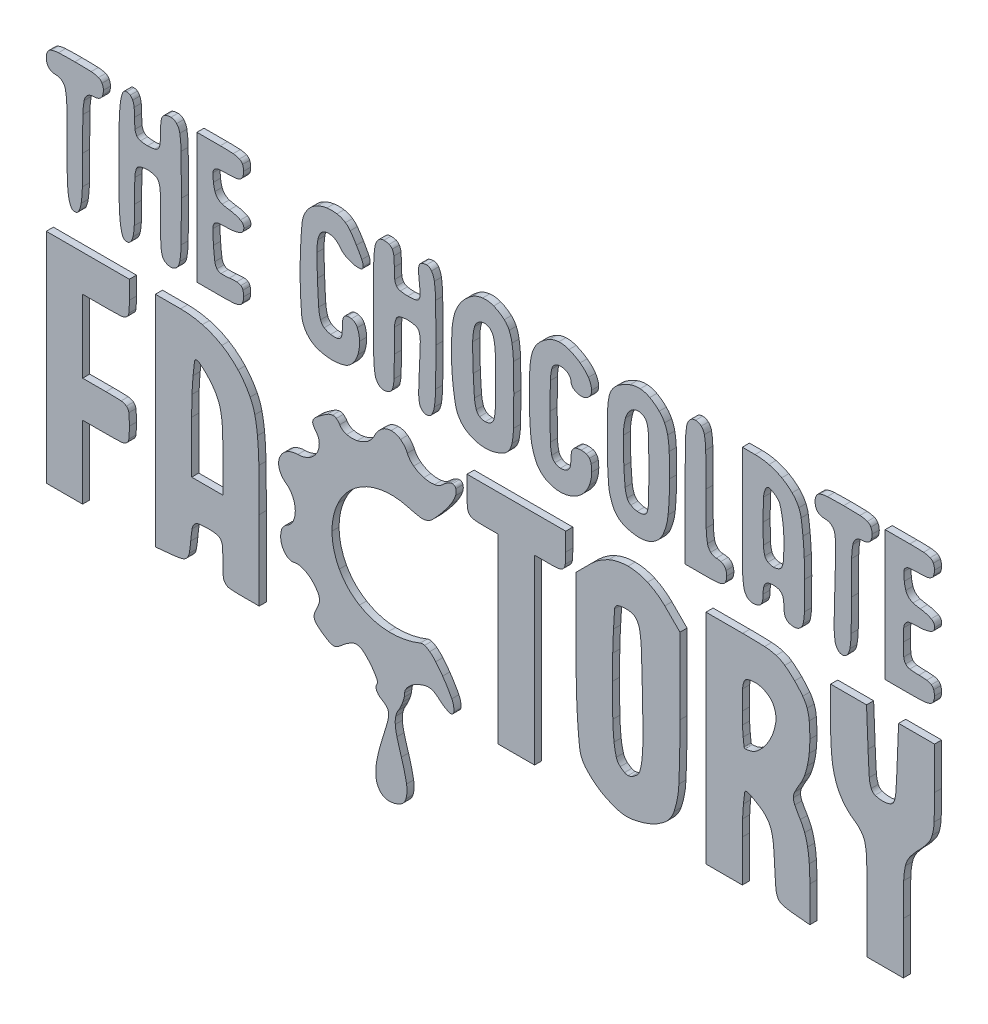
SolidWorks part; units mm, degrees
ref_plane "Front Plane" through (0, 0, 0) normal (0, 0, 1) x (1, 0, 0)
ref_plane "Top Plane" through (0, 0, 0) normal (0, 1, 0) x (1, 0, 0)
ref_plane "Right Plane" through (0, 0, 0) normal (1, 0, 0) x (0, 0, -1)
sketch "Sketch1" plane through (0, 0, 0) normal (0, 0, 1) x (1, 0, 0)
  line L0 (2678.2888, 2844.248) -> (2678.2888, 2825.9727)
  line L1 (2678.2888, 2825.9727) -> (2684.8679, 2825.9727)
  line L2 (2684.8679, 2862.5233) -> (2678.2888, 2862.5233)
  line L3 (2678.2888, 2862.5233) -> (2678.2888, 2844.248)
  line L4 (2815.7191, 2844.248) -> (2815.7191, 2825.9727)
  line L5 (2815.7191, 2825.9727) -> (2821.5672, 2825.9727)
  line L6 (2835.3876, 2862.5233) -> (2831.8013, 2862.5233)
  line L7 (2831.8013, 2862.5233) -> (2831.8013, 2844.248)
  line L8 (2872.007, 2844.248) -> (2872.007, 2825.9727)
  line L9 (2872.007, 2825.9727) -> (2878.9516, 2825.9727)
  line L10 (2878.9516, 2862.5233) -> (2872.007, 2862.5233)
  line L11 (2872.007, 2862.5233) -> (2872.007, 2844.248)
  line L12 (2635.8901, 2786.4981) -> (2635.8901, 2755.7956)
  line L13 (2635.8901, 2755.7956) -> (2641.0072, 2755.7956)
  line L14 (2641.0072, 2755.7956) -> (2646.1243, 2755.7956)
  line L15 (2646.1243, 2755.7956) -> (2646.1243, 2766.0297)
  line L16 (2646.1243, 2766.0297) -> (2646.1243, 2776.2639)
  line L17 (2646.1243, 2776.2639) -> (2652.7034, 2776.2639)
  line L18 (2652.7034, 2786.4981) -> (2646.1243, 2786.4981)
  line L19 (2646.1243, 2786.4981) -> (2646.1243, 2796.7322)
  line L20 (2646.1243, 2796.7322) -> (2646.1243, 2806.9664)
  line L21 (2646.1243, 2806.9664) -> (2652.7034, 2806.9664)
  line L22 (2659.2825, 2812.0835) -> (2659.2825, 2817.2006)
  line L23 (2659.2825, 2817.2006) -> (2647.5863, 2817.2006)
  line L24 (2647.5863, 2817.2006) -> (2635.8901, 2817.2006)
  line L25 (2635.8901, 2817.2006) -> (2635.8901, 2786.4981)
  line L26 (2666.5926, 2786.4054) -> (2666.5926, 2755.6103)
  line L27 (2666.5926, 2755.6103) -> (2671.3442, 2756.0684)
  line L28 (2690.716, 2755.7956) -> (2695.8331, 2755.7956)
  line L29 (2695.8331, 2755.7956) -> (2695.8308, 2778.0914)
  line L30 (2673.6865, 2817.2006) -> (2666.5926, 2817.2006)
  line L31 (2666.5926, 2817.2006) -> (2666.5926, 2786.4054)
  line L32 (2685.5989, 2788.4939) -> (2685.5989, 2777.7259)
  line L33 (2685.5989, 2777.7259) -> (2681.2129, 2777.7259)
  line L34 (2681.2129, 2777.7259) -> (2676.8268, 2777.7259)
  line L35 (2676.8268, 2777.7259) -> (2676.8268, 2792.3462)
  line L36 (2758.7001, 2806.9664) -> (2763.0862, 2806.9664)
  line L37 (2763.0862, 2806.9664) -> (2763.0862, 2781.381)
  line L38 (2763.0862, 2781.381) -> (2763.0862, 2755.7956)
  line L39 (2763.0862, 2755.7956) -> (2768.2033, 2755.7956)
  line L40 (2768.2033, 2755.7956) -> (2773.3204, 2755.7956)
  line L41 (2773.3204, 2755.7956) -> (2773.3204, 2781.381)
  line L42 (2773.3204, 2781.381) -> (2773.3204, 2806.9664)
  line L43 (2773.3204, 2806.9664) -> (2777.7065, 2806.9664)
  line L44 (2782.0925, 2812.0835) -> (2782.0925, 2817.2006)
  line L45 (2782.0925, 2817.2006) -> (2768.2033, 2817.2006)
  line L46 (2768.2033, 2817.2006) -> (2754.3141, 2817.2006)
  line L47 (2754.3141, 2817.2006) -> (2754.3141, 2812.0835)
  line L48 (2789.2902, 2812.927) -> (2785.0166, 2808.6534)
  line L49 (2785.0166, 2808.6534) -> (2785.0166, 2788.1414)
  line L50 (2814.2571, 2787.2901) -> (2814.2571, 2808.6534)
  line L51 (2814.2571, 2808.6534) -> (2809.9834, 2812.927)
  line L52 (2821.5672, 2786.4981) -> (2821.5672, 2755.7956)
  line L53 (2821.5672, 2755.7956) -> (2826.6843, 2755.7956)
  line L54 (2826.6843, 2755.7956) -> (2831.8013, 2755.7956)
  line L55 (2831.8013, 2755.7956) -> (2831.8013, 2767.4918)
  line L56 (2846.0561, 2756.0684) -> (2850.8077, 2755.6103)
  line L57 (2850.8077, 2755.6103) -> (2850.8022, 2765.5716)
  line L58 (2831.9138, 2817.2006) -> (2821.5672, 2817.2006)
  line L59 (2821.5672, 2817.2006) -> (2821.5672, 2786.4981)
  line L60 (2866.8899, 2770.3821) -> (2866.8899, 2755.7956)
  line L61 (2866.8899, 2755.7956) -> (2872.007, 2755.7956)
  line L62 (2872.007, 2755.7956) -> (2877.1241, 2755.7956)
  line L63 (2877.1241, 2755.7956) -> (2877.1241, 2770.3033)
  line L64 (2885.8962, 2805.3919) -> (2885.8962, 2817.2006)
  line L65 (2885.8962, 2817.2006) -> (2880.8432, 2817.2006)
  line L66 (2880.8432, 2817.2006) -> (2875.7902, 2817.2006)
  line L67 (2875.7902, 2817.2006) -> (2875.3606, 2806.6009)
  line L68 (2867.1914, 2806.6009) -> (2866.7618, 2817.2006)
  line L69 (2866.7618, 2817.2006) -> (2861.7088, 2817.2006)
  line L70 (2861.7088, 2817.2006) -> (2856.6557, 2817.2006)
  line L71 (2856.6557, 2817.2006) -> (2856.6557, 2807.0352)
  arc A0 (2635.8901, 2859.5993) -> (2636.0756, 2858.3227) centre (2640.3768, 2859.5993) ccw
  arc A1 (2636.0756, 2858.3227) -> (2636.6211, 2857.4062) centre (2638.1547, 2858.9398) ccw
  arc A2 (2636.6211, 2857.4062) -> (2637.5376, 2856.8607) centre (2638.1547, 2858.9398) ccw
  arc A3 (2637.5376, 2856.8607) -> (2638.8142, 2856.6752) centre (2638.8142, 2861.1619) ccw
  arc A4 (2640.4125, 2856.0324) -> (2638.8142, 2856.6752) centre (2638.8142, 2854.3669) ccw
  arc A5 (2641.3031, 2854.3908) -> (2640.4125, 2856.0324) centre (2638.2855, 2853.816) ccw
  arc A6 (2641.6702, 2850.7788) -> (2641.3031, 2854.3908) centre (2620.7617, 2850.4782) ccw
  arc A7 (2641.7382, 2841.324) -> (2641.6702, 2850.7788) centre (1984.2119, 2841.3244) ccw
  arc A8 (2641.7382, 2841.324) -> (2641.8181, 2833.0782) centre (3067.5965, 2841.3239) ccw
  arc A9 (2641.8181, 2833.0782) -> (2642.1559, 2828.8968) centre (2676.0693, 2833.7415) ccw
  arc A10 (2642.1559, 2828.8968) -> (2642.8054, 2826.6938) centre (2650.0343, 2830.0223) ccw
  arc A11 (2642.8054, 2826.6938) -> (2645.0571, 2826.6938) centre (2643.9313, 2827.2122) ccw
  arc A12 (2645.0571, 2826.6938) -> (2645.7066, 2828.8968) centre (2637.8282, 2830.0223) ccw
  arc A13 (2645.7066, 2828.8968) -> (2646.0445, 2833.0782) centre (2611.7932, 2833.7415) ccw
  arc A14 (2646.0445, 2833.0782) -> (2646.1243, 2841.324) centre (2220.266, 2841.3239) ccw
  arc A15 (2646.1923, 2850.7788) -> (2646.1243, 2841.324) centre (3303.6506, 2841.3244) ccw
  arc A16 (2646.5594, 2854.3908) -> (2646.1923, 2850.7788) centre (2667.1008, 2850.4782) ccw
  arc A17 (2647.45, 2856.0324) -> (2646.5594, 2854.3908) centre (2649.577, 2853.816) ccw
  arc A18 (2649.0483, 2856.6752) -> (2647.45, 2856.0324) centre (2649.0483, 2854.3669) ccw
  arc A19 (2649.0483, 2856.6752) -> (2650.3249, 2856.8607) centre (2649.0483, 2861.1619) ccw
  arc A20 (2650.3249, 2856.8607) -> (2651.2414, 2857.4062) centre (2649.7079, 2858.9398) ccw
  arc A21 (2651.2414, 2857.4062) -> (2651.7869, 2858.3227) centre (2649.7079, 2858.9398) ccw
  arc A22 (2651.7869, 2858.3227) -> (2651.9724, 2859.5993) centre (2647.4857, 2859.5993) ccw
  arc A23 (2651.9724, 2859.5993) -> (2651.6021, 2861.1405) centre (2648.5801, 2859.5993) ccw
  arc A24 (2651.6021, 2861.1405) -> (2650.6017, 2862.0249) centre (2649.9792, 2860.3128) ccw
  arc A25 (2650.6017, 2862.0249) -> (2648.5222, 2862.4334) centre (2648.2531, 2855.5662) ccw
  arc A26 (2648.5222, 2862.4334) -> (2643.9313, 2862.5233) centre (2643.9312, 2745.2773) ccw
  arc A27 (2643.9313, 2862.5233) -> (2639.3403, 2862.4334) centre (2643.9313, 2745.2773) ccw
  arc A28 (2639.3403, 2862.4334) -> (2637.2608, 2862.0249) centre (2639.6094, 2855.5662) ccw
  arc A29 (2637.2608, 2862.0249) -> (2636.2604, 2861.1405) centre (2637.8834, 2860.3128) ccw
  arc A30 (2636.2604, 2861.1405) -> (2635.8901, 2859.5993) centre (2639.2825, 2859.5993) ccw
  arc A31 (2656.3585, 2844.248) -> (2656.4354, 2834.3059) centre (3299.1403, 2844.248) ccw
  arc A32 (2656.4354, 2834.3059) -> (2656.7678, 2829.3841) centre (2703.902, 2835.0402) ccw
  arc A33 (2656.7678, 2829.3841) -> (2657.4028, 2826.7702) centre (2668.0293, 2830.7355) ccw
  arc A34 (2657.4028, 2826.7702) -> (2658.5515, 2825.9727) centre (2658.5515, 2827.1988) ccw
  arc A35 (2658.5515, 2825.9727) -> (2659.6274, 2826.5244) centre (2658.5515, 2827.2976) ccw
  arc A36 (2659.6274, 2826.5244) -> (2660.3007, 2828.0439) centre (2656.3287, 2828.8951) ccw
  arc A37 (2660.3007, 2828.0439) -> (2660.6552, 2830.9244) centre (2644.2722, 2831.4786) ccw
  arc A38 (2660.6552, 2830.9244) -> (2660.7445, 2836.2069) centre (2504.5153, 2836.2068) ccw
  arc A39 (2660.818, 2842.7649) -> (2660.7445, 2836.2069) centre (2953.5946, 2836.2069) ccw
  arc A40 (2661.2406, 2845.0521) -> (2660.818, 2842.7649) centre (2668.1015, 2842.6018) ccw
  arc A41 (2662.288, 2846.0877) -> (2661.2406, 2845.0521) centre (2662.8414, 2844.4804) ccw
  arc A42 (2664.3996, 2846.4411) -> (2662.288, 2846.0877) centre (2664.3996, 2839.9556) ccw
  arc A43 (2666.5112, 2846.0877) -> (2664.3996, 2846.4411) centre (2664.3996, 2839.9556) ccw
  arc A44 (2667.5586, 2845.0521) -> (2666.5112, 2846.0877) centre (2665.9577, 2844.4804) ccw
  arc A45 (2667.9812, 2842.7649) -> (2667.5586, 2845.0521) centre (2660.6976, 2842.6018) ccw
  arc A46 (2668.0547, 2836.2069) -> (2667.9812, 2842.7649) centre (2375.2046, 2836.2069) ccw
  arc A47 (2668.0547, 2836.2069) -> (2668.1343, 2830.1602) centre (2897.7174, 2836.2071) ccw
  arc A48 (2668.1343, 2830.1602) -> (2668.5246, 2827.6175) centre (2678.3674, 2830.4297) ccw
  arc A49 (2668.5246, 2827.6175) -> (2669.4134, 2826.4278) centre (2670.5336, 2828.1915) ccw
  arc A50 (2669.4134, 2826.4278) -> (2670.9787, 2825.9727) centre (2670.9787, 2828.8924) ccw
  arc A51 (2670.9787, 2825.9727) -> (2672.5929, 2826.7136) centre (2670.9787, 2828.1017) ccw
  arc A52 (2672.5929, 2826.7136) -> (2673.4788, 2828.6226) centre (2669.663, 2829.2332) ccw
  arc A53 (2673.4788, 2828.6226) -> (2673.8383, 2832.8429) centre (2645.0693, 2833.1682) ccw
  arc A54 (2673.8383, 2832.8429) -> (2673.9027, 2844.248) centre (1665.2878, 2844.2475) ccw
  arc A55 (2673.9027, 2844.248) -> (2673.8383, 2855.6532) centre (1665.2878, 2844.2485) ccw
  arc A56 (2673.8383, 2855.6532) -> (2673.4788, 2859.8734) centre (2645.0693, 2855.3279) ccw
  arc A57 (2673.4788, 2859.8734) -> (2672.5929, 2861.7825) centre (2669.663, 2859.2629) ccw
  arc A58 (2672.5929, 2861.7825) -> (2670.9787, 2862.5233) centre (2670.9787, 2860.3943) ccw
  arc A59 (2670.9787, 2862.5233) -> (2669.5131, 2862.2641) centre (2670.9787, 2858.2501) ccw
  arc A60 (2669.5131, 2862.2641) -> (2668.629, 2861.5182) centre (2670.0903, 2860.6831) ccw
  arc A61 (2668.629, 2861.5182) -> (2668.1748, 2860.0734) centre (2671.7171, 2859.7536) ccw
  arc A62 (2668.1748, 2860.0734) -> (2668.0547, 2857.4062) centre (2697.7162, 2857.4063) ccw
  arc A63 (2667.9314, 2854.5325) -> (2668.0547, 2857.4062) centre (2634.4933, 2857.4063) ccw
  arc A64 (2667.4281, 2853.1664) -> (2667.9314, 2854.5325) centre (2665.185, 2854.7686) ccw
  arc A65 (2666.3912, 2852.4919) -> (2667.4281, 2853.1664) centre (2666.0499, 2854.1508) ccw
  arc A66 (2664.3996, 2852.2892) -> (2666.3912, 2852.4919) centre (2664.3996, 2862.173) ccw
  arc A67 (2662.408, 2852.4919) -> (2664.3996, 2852.2892) centre (2664.3996, 2862.173) ccw
  arc A68 (2661.3711, 2853.1664) -> (2662.408, 2852.4919) centre (2662.7493, 2854.1508) ccw
  arc A69 (2660.8678, 2854.5325) -> (2661.3711, 2853.1664) centre (2663.6142, 2854.7686) ccw
  arc A70 (2660.7445, 2857.4062) -> (2660.8678, 2854.5325) centre (2694.3059, 2857.4063) ccw
  arc A71 (2660.7445, 2857.4062) -> (2660.6248, 2859.7514) centre (2637.718, 2857.4063) ccw
  arc A72 (2660.6248, 2859.7514) -> (2660.2224, 2861.305) centre (2655.3333, 2859.2097) ccw
  arc A73 (2660.2224, 2861.305) -> (2659.5302, 2862.1928) centre (2658.1891, 2860.4336) ccw
  arc A74 (2659.5302, 2862.1928) -> (2658.5515, 2862.5233) centre (2658.5515, 2860.9089) ccw
  arc A75 (2658.5515, 2862.5233) -> (2657.4028, 2861.7259) centre (2658.5515, 2861.2972) ccw
  arc A76 (2657.4028, 2861.7259) -> (2656.7678, 2859.1119) centre (2668.0293, 2857.7606) ccw
  arc A77 (2656.7678, 2859.1119) -> (2656.4354, 2854.1901) centre (2703.902, 2853.4558) ccw
  arc A78 (2656.4354, 2854.1901) -> (2656.3585, 2844.248) centre (3299.1403, 2844.248) ccw
  arc A79 (2684.8679, 2825.9727) -> (2688.5423, 2826.0736) centre (2684.8679, 2892.9681) ccw
  arc A80 (2688.5423, 2826.0736) -> (2690.2876, 2826.5065) centre (2688.2788, 2830.87) ccw
  arc A81 (2690.2876, 2826.5065) -> (2691.1447, 2827.4125) centre (2689.5874, 2828.0273) ccw
  arc A82 (2691.1447, 2827.4125) -> (2691.447, 2829.0014) centre (2687.1205, 2829.0014) ccw
  arc A83 (2691.447, 2829.0014) -> (2691.2545, 2830.5121) centre (2685.4232, 2829.0014) ccw
  arc A84 (2691.2545, 2830.5121) -> (2690.6531, 2831.3391) centre (2689.9041, 2830.1622) ccw
  arc A85 (2690.6531, 2831.3391) -> (2689.5089, 2831.6757) centre (2689.4973, 2829.523) ccw
  arc A86 (2689.5089, 2831.6757) -> (2687.4265, 2831.5599) centre (2689.4166, 2814.5407) ccw
  arc A87 (2685.0697, 2831.4868) -> (2687.4265, 2831.5599) centre (2685.8205, 2845.2942) ccw
  arc A88 (2683.935, 2832.0802) -> (2685.0697, 2831.4868) centre (2685.1536, 2833.0286) ccw
  arc A89 (2683.3317, 2833.5322) -> (2683.935, 2832.0802) centre (2686.2816, 2833.9065) ccw
  arc A90 (2682.9563, 2837.3034) -> (2683.3317, 2833.5322) centre (2752.9885, 2842.3705) ccw
  arc A91 (2682.7664, 2841.2535) -> (2682.9563, 2837.3034) centre (2764.4968, 2843.2031) ccw
  arc A92 (2683.1693, 2842.6802) -> (2682.7664, 2841.2535) centre (2685.2815, 2841.3135) ccw
  arc A93 (2684.2459, 2843.3527) -> (2683.1693, 2842.6802) centre (2684.4253, 2841.8675) ccw
  arc A94 (2686.9769, 2843.517) -> (2684.2459, 2843.3527) centre (2686.9769, 2820.7422) ccw
  arc A95 (2686.9769, 2843.517) -> (2690.2438, 2844.0443) centre (2686.9769, 2853.9004) ccw
  arc A96 (2690.2438, 2844.0443) -> (2691.4845, 2845.5992) centre (2689.6703, 2845.7744) ccw
  arc A97 (2691.4845, 2845.5992) -> (2690.5406, 2847.2727) centre (2689.815, 2845.7605) ccw
  arc A98 (2690.5406, 2847.2727) -> (2687.4265, 2848.1715) centre (2686.3081, 2838.4522) ccw
  arc A99 (2685.404, 2848.5991) -> (2687.4265, 2848.1715) centre (2688.688, 2859.1354) ccw
  arc A100 (2684.1369, 2849.3651) -> (2685.404, 2848.5991) centre (2686.3247, 2851.5529) ccw
  arc A101 (2683.3709, 2850.6322) -> (2684.1369, 2849.3651) centre (2686.3247, 2851.5529) ccw
  arc A102 (2682.9433, 2852.6547) -> (2683.3709, 2850.6322) centre (2693.9073, 2853.9162) ccw
  arc A103 (2682.8305, 2854.9417) -> (2682.9433, 2852.6547) centre (2700.3809, 2854.6611) ccw
  arc A104 (2683.2871, 2856.0196) -> (2682.8305, 2854.9417) centre (2684.39, 2854.9167) ccw
  arc A105 (2684.4022, 2856.5479) -> (2683.2871, 2856.0196) centre (2684.5842, 2854.7226) ccw
  arc A106 (2686.9639, 2856.6752) -> (2684.4022, 2856.5479) centre (2686.9639, 2830.8495) ccw
  arc A107 (2686.9639, 2856.6752) -> (2689.2207, 2856.8079) centre (2686.9638, 2875.9431) ccw
  arc A108 (2689.2207, 2856.8079) -> (2690.5211, 2857.2791) centre (2688.8658, 2859.8172) ccw
  arc A109 (2690.5211, 2857.2791) -> (2691.2105, 2858.1672) centre (2689.581, 2858.7205) ccw
  arc A110 (2691.2105, 2858.1672) -> (2691.447, 2859.5993) centre (2686.9933, 2859.5993) ccw
  arc A111 (2691.447, 2859.5993) -> (2691.1331, 2861.1132) centre (2687.6395, 2859.5993) ccw
  arc A112 (2691.1331, 2861.1132) -> (2690.2591, 2861.9954) centre (2689.5651, 2860.4337) ccw
  arc A113 (2690.2591, 2861.9954) -> (2688.4929, 2862.4221) centre (2688.2114, 2857.388) ccw
  arc A114 (2688.4929, 2862.4221) -> (2684.8679, 2862.5233) centre (2684.8679, 2797.587) ccw
  arc A115 (2709.9489, 2859.8497) -> (2707.8656, 2855.0896) centre (2716.0173, 2854.3578) ccw
  arc A116 (2707.8656, 2855.0896) -> (2707.3435, 2843.9155) centre (2837.9741, 2843.4102) ccw
  arc A117 (2707.3435, 2843.9155) -> (2707.7652, 2832.7376) centre (2841.8838, 2843.3949) ccw
  arc A118 (2707.7652, 2832.7376) -> (2709.8268, 2828.2702) centre (2714.8578, 2833.3012) ccw
  arc A119 (2709.8268, 2828.2702) -> (2712.487, 2826.6513) centre (2714.4831, 2832.9265) ccw
  arc A120 (2712.487, 2826.6513) -> (2716.1478, 2826.0474) centre (2716.393, 2838.9306) ccw
  arc A121 (2716.1478, 2826.0474) -> (2719.7038, 2826.511) centre (2716.3781, 2838.1501) ccw
  arc A122 (2719.7038, 2826.511) -> (2722.0432, 2828.0377) centre (2718.4048, 2831.0573) ccw
  arc A123 (2722.0432, 2828.0377) -> (2723.6008, 2830.9402) centre (2715.6701, 2833.3269) ccw
  arc A124 (2723.6008, 2830.9402) -> (2724.0787, 2834.481) centre (2712.7414, 2834.2083) ccw
  arc A125 (2724.0787, 2834.481) -> (2723.4336, 2837.4635) centre (2715.9585, 2834.2857) ccw
  arc A126 (2723.4336, 2837.4635) -> (2721.784, 2838.8153) centre (2721.3177, 2836.564) ccw
  arc A127 (2721.784, 2838.8153) -> (2720.5687, 2838.8502) centre (2721.0782, 2835.4078) ccw
  arc A128 (2720.5687, 2838.8502) -> (2719.7829, 2838.3881) centre (2720.7465, 2837.6486) ccw
  arc A129 (2719.7829, 2838.3881) -> (2719.3484, 2837.341) centre (2721.5237, 2837.0521) ccw
  arc A130 (2719.3484, 2837.341) -> (2719.2255, 2835.4814) centre (2733.3504, 2835.4814) ccw
  arc A131 (2719.0899, 2833.4732) -> (2719.2255, 2835.4814) centre (2704.2912, 2835.4814) ccw
  arc A132 (2718.593, 2832.4502) -> (2719.0899, 2833.4732) centre (2717.2836, 2833.7183) ccw
  arc A133 (2717.6401, 2832.0136) -> (2718.593, 2832.4502) centre (2717.5568, 2833.4537) ccw
  arc A134 (2715.9359, 2832.0846) -> (2717.6401, 2832.0136) centre (2717.144, 2840.5904) ccw
  arc A135 (2714.113, 2832.8073) -> (2715.9359, 2832.0846) centre (2716.5248, 2836.2308) ccw
  arc A136 (2713.0839, 2834.216) -> (2714.113, 2832.8073) centre (2715.6807, 2835.0326) ccw
  arc A137 (2712.561, 2837.037) -> (2713.0839, 2834.216) centre (2724.3853, 2837.7699) ccw
  arc A138 (2712.219, 2843.9047) -> (2712.561, 2837.037) centre (2995.3701, 2854.5648) ccw
  arc A139 (2712.0747, 2850.118) -> (2712.219, 2843.9047) centre (2927.6957, 2852.0168) ccw
  arc A140 (2712.3255, 2853.3375) -> (2712.0747, 2850.118) centre (2730.7537, 2850.2825) ccw
  arc A141 (2713.0107, 2855.1688) -> (2712.3255, 2853.3375) centre (2717.3349, 2852.507) ccw
  arc A142 (2714.2579, 2856.2039) -> (2713.0107, 2855.1688) centre (2715.1637, 2853.8435) ccw
  arc A143 (2715.3884, 2856.4188) -> (2714.2579, 2856.2039) centre (2715.4187, 2853.1791) ccw
  arc A144 (2716.5364, 2856.2294) -> (2715.3884, 2856.4188) centre (2715.42, 2853.0373) ccw
  arc A145 (2717.6045, 2855.646) -> (2716.5364, 2856.2294) centre (2715.3019, 2852.6996) ccw
  arc A146 (2718.5016, 2854.7197) -> (2717.6045, 2855.646) centre (2714.7191, 2851.9539) ccw
  arc A147 (2718.5016, 2854.7197) -> (2720.1038, 2853.29) centre (2722.6427, 2857.7478) ccw
  arc A148 (2720.1038, 2853.29) -> (2722.4074, 2852.3739) centre (2724.5249, 2861.0527) ccw
  arc A149 (2722.4074, 2852.3739) -> (2724.348, 2852.2795) centre (2723.6222, 2857.3527) ccw
  arc A150 (2724.348, 2852.2795) -> (2725.0736, 2853.1163) centre (2724.2283, 2853.1163) ccw
  arc A151 (2725.0736, 2853.1163) -> (2724.7009, 2854.6966) centre (2721.5364, 2853.1163) ccw
  arc A152 (2724.7009, 2854.6966) -> (2723.1859, 2857.4588) centre (2688.1073, 2836.4219) ccw
  arc A153 (2723.1859, 2857.4588) -> (2721.4455, 2860.1069) centre (2690.2261, 2837.6926) ccw
  arc A154 (2721.4455, 2860.1069) -> (2720.1031, 2861.4044) centre (2717.2029, 2857.0608) ccw
  arc A155 (2720.1031, 2861.4044) -> (2717.7133, 2862.352) centre (2716.6985, 2856.3055) ccw
  arc A156 (2717.7133, 2862.352) -> (2714.8778, 2862.3724) centre (2716.2321, 2853.5268) ccw
  arc A157 (2714.8778, 2862.3724) -> (2712.1181, 2861.4959) centre (2716.2917, 2853.1381) ccw
  arc A158 (2712.1181, 2861.4959) -> (2709.9489, 2859.8497) centre (2715.4066, 2854.9106) ccw
  arc A159 (2727.9976, 2844.248) -> (2728.0621, 2832.8429) centre (3736.6125, 2844.2475) ccw
  arc A160 (2728.0621, 2832.8429) -> (2728.4216, 2828.6226) centre (2756.8311, 2833.1682) ccw
  arc A161 (2728.4216, 2828.6226) -> (2729.3075, 2826.7136) centre (2732.2373, 2829.2332) ccw
  arc A162 (2729.3075, 2826.7136) -> (2730.9217, 2825.9727) centre (2730.9217, 2828.1017) ccw
  arc A163 (2730.9217, 2825.9727) -> (2732.4869, 2826.4278) centre (2730.9217, 2828.8924) ccw
  arc A164 (2732.4869, 2826.4278) -> (2733.3758, 2827.6175) centre (2731.3668, 2828.1915) ccw
  arc A165 (2733.3758, 2827.6175) -> (2733.7661, 2830.1602) centre (2723.533, 2830.4297) ccw
  arc A166 (2733.7661, 2830.1602) -> (2733.8457, 2836.2069) centre (2504.183, 2836.2071) ccw
  arc A167 (2733.9184, 2842.8327) -> (2733.8457, 2836.2069) centre (3035.8677, 2836.207) ccw
  arc A168 (2734.3461, 2845.0847) -> (2733.9184, 2842.8327) centre (2740.8645, 2842.6802) ccw
  arc A169 (2735.4144, 2846.1023) -> (2734.3461, 2845.0847) centre (2735.9167, 2844.5053) ccw
  arc A170 (2737.6208, 2846.4411) -> (2735.4144, 2846.1023) centre (2737.6208, 2839.0875) ccw
  arc A171 (2739.8415, 2846.1184) -> (2737.6208, 2846.4411) centre (2737.6208, 2838.6385) ccw
  arc A172 (2740.8507, 2845.1313) -> (2739.8415, 2846.1184) centre (2739.4111, 2844.6687) ccw
  arc A173 (2741.1628, 2842.9441) -> (2740.8507, 2845.1313) centre (2734.6049, 2843.1244) ccw
  arc A174 (2740.9103, 2836.2036) -> (2741.1628, 2842.9441) centre (2402.327, 2852.2601) ccw
  arc A175 (2740.9103, 2836.2036) -> (2740.711, 2830.3611) centre (2960.6424, 2825.7836) ccw
  arc A176 (2740.711, 2830.3611) -> (2740.9477, 2827.725) centre (2752.7269, 2830.111) ccw
  arc A177 (2740.9477, 2827.725) -> (2741.6765, 2826.4629) centre (2743.1923, 2828.1797) ccw
  arc A178 (2741.6765, 2826.4629) -> (2742.9834, 2825.9694) centre (2742.9808, 2827.9402) ccw
  arc A179 (2742.9834, 2825.9694) -> (2744.3621, 2826.7593) centre (2742.9813, 2827.5712) ccw
  arc A180 (2744.3621, 2826.7593) -> (2745.1252, 2828.9489) centre (2739.2372, 2829.7731) ccw
  arc A181 (2745.1252, 2828.9489) -> (2745.4718, 2833.4979) centre (2709.2517, 2833.9703) ccw
  arc A182 (2745.4718, 2833.4979) -> (2745.5419, 2844.248) centre (1921.1217, 2844.2483) ccw
  arc A183 (2745.5419, 2844.248) -> (2745.473, 2855.1387) centre (1884.4608, 2844.2478) ccw
  arc A184 (2745.473, 2855.1387) -> (2745.1238, 2859.6185) centre (2710.968, 2854.7022) ccw
  arc A185 (2745.1238, 2859.6185) -> (2744.3357, 2861.7423) centre (2739.8044, 2858.8528) ccw
  arc A186 (2744.3357, 2861.7423) -> (2742.9115, 2862.5233) centre (2742.9114, 2860.8341) ccw
  arc A187 (2742.9115, 2862.5233) -> (2741.6226, 2862.2613) centre (2742.9114, 2859.2224) ccw
  arc A188 (2741.6226, 2862.2613) -> (2740.9077, 2861.5298) centre (2742.1406, 2861.0399) ccw
  arc A189 (2740.9077, 2861.5298) -> (2740.6656, 2860.1073) centre (2744.1301, 2860.2495) ccw
  arc A190 (2740.6656, 2860.1073) -> (2740.8784, 2857.4062) centre (2776.6719, 2861.585) ccw
  arc A191 (2741.1257, 2854.3738) -> (2740.8784, 2857.4062) centre (2697.4831, 2852.3401) ccw
  arc A192 (2740.7872, 2853.0877) -> (2741.1257, 2854.3738) centre (2738.9063, 2854.2704) ccw
  arc A193 (2739.8335, 2852.4591) -> (2740.7872, 2853.0877) centre (2739.619, 2853.8222) ccw
  arc A194 (2737.6607, 2852.2892) -> (2739.8335, 2852.4591) centre (2737.6608, 2866.2663) ccw
  arc A195 (2735.5501, 2852.482) -> (2737.6607, 2852.2892) centre (2737.6607, 2863.936) ccw
  arc A196 (2734.4837, 2853.1449) -> (2735.5501, 2852.482) centre (2735.8616, 2854.1721) ccw
  arc A197 (2733.97, 2854.4974) -> (2734.4837, 2853.1449) centre (2736.5997, 2854.7225) ccw
  arc A198 (2733.8457, 2857.4062) -> (2733.97, 2854.4974) centre (2767.951, 2857.4062) ccw
  arc A199 (2733.8457, 2857.4062) -> (2733.7256, 2860.0734) centre (2704.1842, 2857.4063) ccw
  arc A200 (2733.7256, 2860.0734) -> (2733.2714, 2861.5182) centre (2730.1833, 2859.7536) ccw
  arc A201 (2733.2714, 2861.5182) -> (2732.3873, 2862.2641) centre (2731.8101, 2860.6831) ccw
  arc A202 (2732.3873, 2862.2641) -> (2730.9217, 2862.5233) centre (2730.9217, 2858.2501) ccw
  arc A203 (2730.9217, 2862.5233) -> (2729.3075, 2861.7825) centre (2730.9217, 2860.3943) ccw
  arc A204 (2729.3075, 2861.7825) -> (2728.4216, 2859.8734) centre (2732.2373, 2859.2629) ccw
  arc A205 (2728.4216, 2859.8734) -> (2728.0621, 2855.6532) centre (2756.8311, 2855.3279) ccw
  arc A206 (2728.0621, 2855.6532) -> (2727.9976, 2844.248) centre (3736.6125, 2844.2485) ccw
  arc A207 (2752.9582, 2858.6711) -> (2751.4469, 2856.2223) centre (2762.9368, 2850.8219) ccw
  arc A208 (2751.4469, 2856.2223) -> (2750.5373, 2853.5111) centre (2762.6581, 2850.9529) ccw
  arc A209 (2750.5373, 2853.5111) -> (2750.074, 2849.9033) centre (2772.724, 2848.8284) ccw
  arc A210 (2750.074, 2849.9033) -> (2749.9495, 2844.4164) centre (2860.8505, 2844.6462) ccw
  arc A211 (2749.9495, 2844.4164) -> (2750.093, 2840.1658) centre (2817.1035, 2844.5555) ccw
  arc A212 (2750.093, 2840.1658) -> (2750.5052, 2835.9959) centre (2813.2325, 2844.3019) ccw
  arc A213 (2750.5052, 2835.9959) -> (2751.0975, 2832.4289) centre (2804.9971, 2843.2114) ccw
  arc A214 (2751.0975, 2832.4289) -> (2751.811, 2830.3588) centre (2759.1062, 2834.031) ccw
  arc A215 (2751.811, 2830.3588) -> (2753.949, 2827.8458) centre (2758.0453, 2833.497) ccw
  arc A216 (2753.949, 2827.8458) -> (2757.1489, 2826.384) centre (2759.1787, 2835.0606) ccw
  arc A217 (2757.1489, 2826.384) -> (2760.87, 2826.2175) centre (2759.4541, 2836.2381) ccw
  arc A218 (2760.87, 2826.2175) -> (2764.4759, 2827.3961) centre (2759.3502, 2836.9735) ccw
  arc A219 (2764.4759, 2827.3961) -> (2766.1011, 2828.8713) centre (2762.3468, 2831.3744) ccw
  arc A220 (2766.1011, 2828.8713) -> (2766.9895, 2831.0519) centre (2761.1981, 2832.1402) ccw
  arc A221 (2766.9895, 2831.0519) -> (2767.3865, 2834.8916) centre (2744.033, 2835.3657) ccw
  arc A222 (2767.3865, 2834.8916) -> (2767.4723, 2843.3419) centre (2351.1708, 2843.3416) ccw
  arc A223 (2767.4723, 2843.3419) -> (2767.3726, 2851.1782) centre (2459.4043, 2843.342) ccw
  arc A224 (2767.3726, 2851.1782) -> (2766.977, 2855.4754) centre (2734.8491, 2850.3506) ccw
  arc A225 (2766.977, 2855.4754) -> (2766.1824, 2858.182) centre (2756.0119, 2853.7263) ccw
  arc A226 (2766.1824, 2858.182) -> (2764.7986, 2860.1037) centre (2761.008, 2855.915) ccw
  arc A227 (2764.7986, 2860.1037) -> (2761.8205, 2861.9562) centre (2758.1931, 2852.8047) ccw
  arc A228 (2761.8205, 2861.9562) -> (2758.721, 2862.3566) centre (2759.483, 2856.0589) ccw
  arc A229 (2758.721, 2862.3566) -> (2755.7011, 2861.2266) centre (2759.5435, 2855.5589) ccw
  arc A230 (2755.7011, 2861.2266) -> (2752.9582, 2858.6711) centre (2762.547, 2851.1286) ccw
  arc A231 (2762.28, 2837.2219) -> (2762.3552, 2844.228) centre (2435.8553, 2844.2281) ccw
  arc A232 (2761.8982, 2834.3769) -> (2762.28, 2837.2219) centre (2749.4366, 2837.4976) ccw
  arc A233 (2761.0074, 2833.0616) -> (2761.8982, 2834.3769) centre (2759.6507, 2834.9397) ccw
  arc A234 (2759.4312, 2832.5518) -> (2761.0074, 2833.0616) centre (2759.4312, 2835.2437) ccw
  arc A235 (2757.8644, 2833.015) -> (2759.4312, 2832.5518) centre (2759.4311, 2835.4331) ccw
  arc A236 (2756.9215, 2834.2331) -> (2757.8644, 2833.015) centre (2759.1306, 2834.9691) ccw
  arc A237 (2756.4086, 2836.8017) -> (2756.9215, 2834.2331) centre (2766.927, 2837.5667) ccw
  arc A238 (2756.0698, 2842.6409) -> (2756.4086, 2836.8017) centre (2955.6826, 2851.2936) ccw
  arc A239 (2755.9041, 2850.2828) -> (2756.0698, 2842.6409) centre (2932.5167, 2850.2892) ccw
  arc A240 (2756.4228, 2854.1863) -> (2755.9041, 2850.2828) centre (2770.8468, 2850.2833) ccw
  arc A241 (2757.7059, 2855.9747) -> (2756.4228, 2854.1863) centre (2759.454, 2853.3661) ccw
  arc A242 (2759.7922, 2856.3978) -> (2757.7059, 2855.9747) centre (2759.2632, 2853.6507) ccw
  arc A243 (2761.1171, 2855.5801) -> (2759.7922, 2856.3978) centre (2759.3774, 2854.2435) ccw
  arc A244 (2761.894, 2853.8919) -> (2761.1171, 2855.5801) centre (2757.7967, 2853.029) ccw
  arc A245 (2762.2686, 2850.7094) -> (2761.894, 2853.8919) centre (2744.5303, 2850.2351) ccw
  arc A246 (2762.3552, 2844.228) -> (2762.2686, 2850.7094) centre (2519.864, 2844.2279) ccw
  arc A247 (2774.7824, 2859.5993) -> (2773.2738, 2857.518) centre (2780.5519, 2853.8297) ccw
  arc A248 (2773.2738, 2857.518) -> (2772.4005, 2854.9736) centre (2781.9692, 2853.1115) ccw
  arc A249 (2772.4005, 2854.9736) -> (2771.9706, 2851.1879) centre (2796.0567, 2850.3701) ccw
  arc A250 (2771.9706, 2851.1879) -> (2771.8584, 2844.5733) centre (2966.7909, 2844.5733) ccw
  arc A251 (2771.8584, 2844.5733) -> (2772.2685, 2835.4736) centre (2872.9997, 2844.5733) ccw
  arc A252 (2772.2685, 2835.4736) -> (2773.7335, 2830.0151) centre (2788.7004, 2836.958) ccw
  arc A253 (2773.7335, 2830.0151) -> (2776.422, 2827.0676) centre (2779.7571, 2832.8093) ccw
  arc A254 (2776.422, 2827.0676) -> (2780.4868, 2825.9727) centre (2780.4868, 2834.0657) ccw
  arc A255 (2780.4868, 2825.9727) -> (2783.9398, 2826.6691) centre (2780.4868, 2834.8817) ccw
  arc A256 (2783.9398, 2826.6691) -> (2786.8254, 2828.6474) centre (2780.5762, 2834.669) ccw
  arc A257 (2786.8254, 2828.6474) -> (2788.7344, 2831.6407) centre (2780.3637, 2834.8738) ccw
  arc A258 (2788.7344, 2831.6407) -> (2789.4026, 2835.2255) centre (2779.4531, 2835.2255) ccw
  arc A259 (2789.4026, 2835.2255) -> (2789.255, 2837.1129) centre (2777.2681, 2835.2255) ccw
  arc A260 (2789.255, 2837.1129) -> (2788.7635, 2838.2773) centre (2786.6633, 2836.7049) ccw
  arc A261 (2788.7635, 2838.2773) -> (2787.8688, 2838.9142) centre (2787.3199, 2837.1964) ccw
  arc A262 (2787.8688, 2838.9142) -> (2786.4786, 2839.1309) centre (2786.4786, 2834.5636) ccw
  arc A263 (2786.4786, 2839.1309) -> (2785.1112, 2838.9225) centre (2786.4786, 2834.5416) ccw
  arc A264 (2785.1112, 2838.9225) -> (2784.2125, 2838.3086) centre (2785.6657, 2837.1459) ccw
  arc A265 (2784.2125, 2838.3086) -> (2783.7102, 2837.2051) centre (2786.1439, 2836.7634) ccw
  arc A266 (2783.7102, 2837.2051) -> (2783.5545, 2835.4759) centre (2793.2376, 2835.4759) ccw
  arc A267 (2783.3989, 2833.7466) -> (2783.5545, 2835.4759) centre (2773.8715, 2835.4759) ccw
  arc A268 (2782.8966, 2832.6432) -> (2783.3989, 2833.7466) centre (2780.9652, 2834.1884) ccw
  arc A269 (2781.9979, 2832.0293) -> (2782.8966, 2832.6432) centre (2781.4434, 2833.8058) ccw
  arc A270 (2780.6305, 2831.8208) -> (2781.9979, 2832.0293) centre (2780.6305, 2836.4101) ccw
  arc A271 (2779.0493, 2832.3586) -> (2780.6305, 2831.8208) centre (2780.6305, 2834.4143) ccw
  arc A272 (2778.158, 2833.7397) -> (2779.0493, 2832.3586) centre (2780.5433, 2834.301) ccw
  arc A273 (2777.7798, 2836.7419) -> (2778.158, 2833.7397) centre (2792.1067, 2837.0218) ccw
  arc A274 (2777.7065, 2844.248) -> (2777.7798, 2836.7419) centre (3161.9565, 2844.2479) ccw
  arc A275 (2777.7798, 2851.7542) -> (2777.7065, 2844.248) centre (3161.9565, 2844.2481) ccw
  arc A276 (2778.158, 2854.7563) -> (2777.7798, 2851.7542) centre (2792.1067, 2851.4743) ccw
  arc A277 (2779.0493, 2856.1375) -> (2778.158, 2854.7563) centre (2780.5433, 2854.1951) ccw
  arc A278 (2780.6305, 2856.6752) -> (2779.0493, 2856.1375) centre (2780.6305, 2854.0818) ccw
  arc A279 (2781.7554, 2856.5117) -> (2780.6305, 2856.6752) centre (2780.6305, 2852.7249) ccw
  arc A280 (2782.7017, 2856.0356) -> (2781.7554, 2856.5117) centre (2780.9006, 2853.6341) ccw
  arc A281 (2783.3306, 2855.324) -> (2782.7017, 2856.0356) centre (2781.2925, 2854.1566) ccw
  arc A282 (2783.5545, 2854.4822) -> (2783.3306, 2855.324) centre (2781.8609, 2854.4822) ccw
  arc A283 (2783.5545, 2854.4822) -> (2783.7785, 2853.6404) centre (2785.2482, 2854.4822) ccw
  arc A284 (2783.7785, 2853.6404) -> (2784.4074, 2852.9288) centre (2785.8166, 2854.8077) ccw
  arc A285 (2784.4074, 2852.9288) -> (2785.3537, 2852.4527) centre (2786.2085, 2855.3303) ccw
  arc A286 (2785.3537, 2852.4527) -> (2786.4786, 2852.2892) centre (2786.4786, 2856.2395) ccw
  arc A287 (2786.4786, 2852.2892) -> (2788.5704, 2853.1429) centre (2786.4786, 2855.2786) ccw
  arc A288 (2788.5704, 2853.1429) -> (2789.3782, 2855.1803) centre (2786.6828, 2855.0701) ccw
  arc A289 (2789.3782, 2855.1803) -> (2788.4838, 2857.8856) centre (2784.1988, 2854.9685) ccw
  arc A290 (2788.4838, 2857.8856) -> (2786.1533, 2860.2474) centre (2780.8673, 2852.7006) ccw
  arc A291 (2786.1533, 2860.2474) -> (2783.0111, 2861.9321) centre (2777.5283, 2847.9334) ccw
  arc A292 (2783.0111, 2861.9321) -> (2780.1451, 2862.3893) centre (2780.5319, 2855.6023) ccw
  arc A293 (2780.1451, 2862.3893) -> (2777.4407, 2861.6052) centre (2780.5038, 2856.0963) ccw
  arc A294 (2777.4407, 2861.6052) -> (2774.7824, 2859.5993) centre (2783.2821, 2851.0996) ccw
  arc A295 (2797.0381, 2860.2474) -> (2795.2592, 2858.4448) centre (2801.0732, 2854.4864) ccw
  arc A296 (2795.2592, 2858.4448) -> (2794.3029, 2856.1826) centre (2800.4245, 2854.9281) ccw
  arc A297 (2794.3029, 2856.1826) -> (2793.8814, 2852.4531) centre (2814.8542, 2851.9709) ccw
  arc A298 (2793.8814, 2852.4531) -> (2793.7887, 2844.3917) centre (3144.5632, 2844.3914) ccw
  arc A299 (2793.7887, 2844.3917) -> (2794.1542, 2834.7123) centre (2922.1435, 2844.3918) ccw
  arc A300 (2794.1542, 2834.7123) -> (2795.5736, 2829.5578) centre (2808.0358, 2835.7621) ccw
  arc A301 (2795.5736, 2829.5578) -> (2798.3648, 2826.9184) centre (2800.5688, 2832.0447) ccw
  arc A302 (2798.3648, 2826.9184) -> (2802.9586, 2825.9727) centre (2802.9586, 2837.6032) ccw
  arc A303 (2802.9586, 2825.9727) -> (2806.8619, 2827.091) centre (2802.9586, 2833.3439) ccw
  arc A304 (2806.8619, 2827.091) -> (2809.4799, 2830.0887) centre (2803.2357, 2832.9) ccw
  arc A305 (2809.4799, 2830.0887) -> (2810.9241, 2835.5844) centre (2793.8072, 2837.1449) ccw
  arc A306 (2810.9241, 2835.5844) -> (2811.333, 2844.5733) centre (2712.3263, 2844.5734) ccw
  arc A307 (2811.333, 2844.5733) -> (2811.2207, 2851.1879) centre (2616.4004, 2844.5733) ccw
  arc A308 (2811.2207, 2851.1879) -> (2810.7909, 2854.9736) centre (2787.1346, 2850.3701) ccw
  arc A309 (2810.7909, 2854.9736) -> (2809.9176, 2857.518) centre (2801.2222, 2853.1115) ccw
  arc A310 (2809.9176, 2857.518) -> (2808.409, 2859.5993) centre (2802.6394, 2853.8297) ccw
  arc A311 (2808.409, 2859.5993) -> (2805.7507, 2861.6052) centre (2799.9092, 2851.0996) ccw
  arc A312 (2805.7507, 2861.6052) -> (2803.0463, 2862.3893) centre (2802.6876, 2856.0963) ccw
  arc A313 (2803.0463, 2862.3893) -> (2800.1802, 2861.9321) centre (2802.6594, 2855.6023) ccw
  arc A314 (2800.1802, 2861.9321) -> (2797.0381, 2860.2474) centre (2805.6631, 2847.9334) ccw
  arc A315 (2805.4212, 2836.0923) -> (2805.4849, 2844.1463) centre (2296.3564, 2844.1465) ccw
  arc A316 (2805.0371, 2833.3867) -> (2805.4212, 2836.0923) centre (2794.4821, 2836.2654) ccw
  arc A317 (2804.0493, 2832.2946) -> (2805.0371, 2833.3867) centre (2803.4654, 2833.8154) ccw
  arc A318 (2802.1954, 2832.0846) -> (2804.0493, 2832.2946) centre (2802.7177, 2835.7628) ccw
  arc A319 (2800.4121, 2832.715) -> (2802.1954, 2832.0846) centre (2802.8691, 2836.8284) ccw
  arc A320 (2799.3774, 2833.9199) -> (2800.4121, 2832.715) centre (2801.6956, 2834.8638) ccw
  arc A321 (2798.816, 2836.2283) -> (2799.3774, 2833.9199) centre (2806.8346, 2836.9562) ccw
  arc A322 (2798.4582, 2841.2631) -> (2798.816, 2836.2283) centre (2927.075, 2847.8709) ccw
  arc A323 (2798.3126, 2848.7077) -> (2798.4582, 2841.2631) centre (2915.5282, 2847.2777) ccw
  arc A324 (2798.9382, 2853.245) -> (2798.3126, 2848.7077) centre (2816.7055, 2848.4833) ccw
  arc A325 (2800.3548, 2855.7337) -> (2798.9382, 2853.245) centre (2804.4082, 2851.779) ccw
  arc A326 (2802.5887, 2856.6752) -> (2800.3548, 2855.7337) centre (2802.5887, 2853.5542) ccw
  arc A327 (2804.1512, 2856.1292) -> (2802.5887, 2856.6752) centre (2802.5887, 2854.1664) ccw
  arc A328 (2805.0349, 2854.7285) -> (2804.1512, 2856.1292) centre (2802.5855, 2854.1623) ccw
  arc A329 (2805.4115, 2851.6904) -> (2805.0349, 2854.7285) centre (2790.6487, 2851.403) ccw
  arc A330 (2805.4849, 2844.1463) -> (2805.4115, 2851.6904) centre (2417.9457, 2844.1467) ccw
  arc A331 (2821.5672, 2825.9727) -> (2824.7117, 2826.0821) centre (2821.5672, 2871.2256) ccw
  arc A332 (2824.7117, 2826.0821) -> (2826.3187, 2826.521) centre (2824.4161, 2830.3263) ccw
  arc A333 (2826.3187, 2826.521) -> (2827.129, 2827.4032) centre (2825.5668, 2828.0248) ccw
  arc A334 (2827.129, 2827.4032) -> (2827.4153, 2828.8968) centre (2823.3754, 2828.8968) ccw
  arc A335 (2827.4153, 2828.8968) -> (2827.2298, 2830.1734) centre (2822.9286, 2828.8968) ccw
  arc A336 (2827.2298, 2830.1734) -> (2826.6843, 2831.0898) centre (2825.1507, 2829.5563) ccw
  arc A337 (2826.6843, 2831.0898) -> (2825.7678, 2831.6354) centre (2825.1507, 2829.5563) ccw
  arc A338 (2825.7678, 2831.6354) -> (2824.4912, 2831.8208) centre (2824.4912, 2827.3342) ccw
  arc A339 (2822.8929, 2832.4637) -> (2824.4912, 2831.8208) centre (2824.4912, 2834.1292) ccw
  arc A340 (2822.0023, 2834.1052) -> (2822.8929, 2832.4637) centre (2825.0198, 2834.68) ccw
  arc A341 (2821.6351, 2837.7172) -> (2822.0023, 2834.1052) centre (2842.5437, 2838.0179) ccw
  arc A342 (2821.5672, 2847.1721) -> (2821.6351, 2837.7172) centre (3479.0935, 2847.1717) ccw
  arc A343 (2821.5672, 2847.1721) -> (2821.4992, 2856.6269) centre (2164.0408, 2847.1725) ccw
  arc A344 (2821.4992, 2856.6269) -> (2821.132, 2860.2389) centre (2800.5907, 2856.3263) ccw
  arc A345 (2821.132, 2860.2389) -> (2820.2414, 2861.8805) centre (2818.1145, 2859.6641) ccw
  arc A346 (2820.2414, 2861.8805) -> (2818.6431, 2862.5233) centre (2818.6431, 2860.215) ccw
  arc A347 (2818.6431, 2862.5233) -> (2817.0289, 2861.7825) centre (2818.6431, 2860.3943) ccw
  arc A348 (2817.0289, 2861.7825) -> (2816.1431, 2859.8734) centre (2819.9588, 2859.2629) ccw
  arc A349 (2816.1431, 2859.8734) -> (2815.7836, 2855.6532) centre (2844.5525, 2855.3279) ccw
  arc A350 (2815.7836, 2855.6532) -> (2815.7191, 2844.248) centre (3824.334, 2844.2485) ccw
  arc A351 (2831.8013, 2844.248) -> (2831.8658, 2832.8429) centre (3840.4162, 2844.2475) ccw
  arc A352 (2831.8658, 2832.8429) -> (2832.2253, 2828.6226) centre (2860.6348, 2833.1682) ccw
  arc A353 (2832.2253, 2828.6226) -> (2833.1112, 2826.7136) centre (2836.041, 2829.2332) ccw
  arc A354 (2833.1112, 2826.7136) -> (2834.7254, 2825.9727) centre (2834.7254, 2828.1017) ccw
  arc A355 (2834.7254, 2825.9727) -> (2836.0928, 2826.1812) centre (2834.7254, 2830.562) ccw
  arc A356 (2836.0928, 2826.1812) -> (2836.9915, 2826.7951) centre (2835.5382, 2827.9577) ccw
  arc A357 (2836.9915, 2826.7951) -> (2837.4938, 2827.8986) centre (2835.0601, 2828.3403) ccw
  arc A358 (2837.4938, 2827.8986) -> (2837.6494, 2829.6278) centre (2827.9664, 2829.6278) ccw
  arc A359 (2837.8051, 2831.357) -> (2837.6494, 2829.6278) centre (2847.3324, 2829.6278) ccw
  arc A360 (2838.3073, 2832.4605) -> (2837.8051, 2831.357) centre (2840.2388, 2830.9153) ccw
  arc A361 (2839.2061, 2833.0744) -> (2838.3073, 2832.4605) centre (2839.7606, 2831.2978) ccw
  arc A362 (2840.5735, 2833.2828) -> (2839.2061, 2833.0744) centre (2840.5735, 2828.6935) ccw
  arc A363 (2841.9409, 2833.0744) -> (2840.5735, 2833.2828) centre (2840.5735, 2828.6935) ccw
  arc A364 (2842.8396, 2832.4605) -> (2841.9409, 2833.0744) centre (2841.3863, 2831.2978) ccw
  arc A365 (2843.3419, 2831.357) -> (2842.8396, 2832.4605) centre (2840.9082, 2830.9153) ccw
  arc A366 (2843.4975, 2829.6278) -> (2843.3419, 2831.357) centre (2833.8145, 2829.6278) ccw
  arc A367 (2843.4975, 2829.6278) -> (2843.6532, 2827.8986) centre (2853.1805, 2829.6278) ccw
  arc A368 (2843.6532, 2827.8986) -> (2844.1554, 2826.7951) centre (2846.0869, 2828.3403) ccw
  arc A369 (2844.1554, 2826.7951) -> (2845.0542, 2826.1812) centre (2845.6087, 2827.9577) ccw
  arc A370 (2845.0542, 2826.1812) -> (2846.4216, 2825.9727) centre (2846.4216, 2830.562) ccw
  arc A371 (2846.4216, 2825.9727) -> (2848.0069, 2826.5349) centre (2846.4216, 2828.4892) ccw
  arc A372 (2848.0069, 2826.5349) -> (2848.8985, 2827.9744) centre (2846.3834, 2828.5362) ccw
  arc A373 (2848.8985, 2827.9744) -> (2849.2737, 2831.1149) centre (2833.5685, 2831.399) ccw
  arc A374 (2849.2737, 2831.1149) -> (2849.3456, 2839.0621) centre (2409.9503, 2839.0622) ccw
  arc A375 (2849.3456, 2839.0621) -> (2849.2265, 2844.3347) centre (2732.5584, 2839.0622) ccw
  arc A376 (2849.2265, 2844.3347) -> (2848.8688, 2849.3531) centre (2752.5866, 2839.9674) ccw
  arc A377 (2848.8688, 2849.3531) -> (2848.354, 2853.5711) centre (2761.7196, 2840.8577) ccw
  arc A378 (2848.354, 2853.5711) -> (2847.7224, 2855.7142) centre (2840.484, 2852.4162) ccw
  arc A379 (2847.7224, 2855.7142) -> (2845.8259, 2858.4285) centre (2839.4137, 2851.9285) ccw
  arc A380 (2845.8259, 2858.4285) -> (2842.9005, 2860.6134) centre (2836.445, 2848.9192) ccw
  arc A381 (2842.9005, 2860.6134) -> (2839.29, 2862.0382) centre (2835.5826, 2847.3569) ccw
  arc A382 (2839.29, 2862.0382) -> (2835.3876, 2862.5233) centre (2835.3876, 2846.5847) ccw
  arc A383 (2842.4236, 2853.7686) -> (2841.7431, 2854.9208) centre (2839.8448, 2853.0225) ccw
  arc A384 (2842.9822, 2851.4055) -> (2842.4236, 2853.7686) centre (2818.8712, 2846.9543) ccw
  arc A385 (2843.3688, 2848.5128) -> (2842.9822, 2851.4055) centre (2814.0989, 2846.0732) ccw
  arc A386 (2843.4975, 2845.4176) -> (2843.3688, 2848.5128) centre (2806.2329, 2845.4176) ccw
  arc A387 (2843.4057, 2841.0203) -> (2843.4975, 2845.4176) centre (2738.1318, 2845.4176) ccw
  arc A388 (2842.9941, 2839.003) -> (2843.4057, 2841.0203) centre (2836.9317, 2841.2907) ccw
  arc A389 (2842.1103, 2838.0279) -> (2842.9941, 2839.003) centre (2841.3154, 2839.6365) ccw
  arc A390 (2840.5735, 2837.6689) -> (2842.1103, 2838.0279) centre (2840.5735, 2841.1378) ccw
  arc A391 (2839.0149, 2838.0958) -> (2840.5735, 2837.6689) centre (2840.5735, 2840.7274) ccw
  arc A392 (2838.1274, 2839.2223) -> (2839.0149, 2838.0958) centre (2840.0285, 2839.8073) ccw
  arc A393 (2837.7319, 2841.6112) -> (2838.1274, 2839.2223) centre (2846.7617, 2841.879) ccw
  arc A394 (2837.6494, 2847.1721) -> (2837.7319, 2841.6112) centre (3025.1932, 2847.1719) ccw
  arc A395 (2837.7874, 2853.3564) -> (2837.6494, 2847.1721) centre (2976.3141, 2847.1722) ccw
  arc A396 (2838.4636, 2855.845) -> (2837.7874, 2853.3564) centre (2843.6713, 2853.0938) ccw
  arc A397 (2839.7296, 2856.2899) -> (2838.4636, 2855.845) centre (2839.3369, 2855.3836) ccw
  arc A398 (2841.7431, 2854.9208) -> (2839.7296, 2856.2899) centre (2837.1434, 2850.3211) ccw
  arc A399 (2852.2697, 2859.5993) -> (2852.458, 2858.3085) centre (2856.788, 2859.5993) ccw
  arc A400 (2852.458, 2858.3085) -> (2853.0124, 2857.3948) centre (2854.4822, 2858.9119) ccw
  arc A401 (2853.0124, 2857.3948) -> (2853.9539, 2856.8562) centre (2854.5382, 2858.9697) ccw
  arc A402 (2853.9539, 2856.8562) -> (2855.2878, 2856.6752) centre (2855.2878, 2861.6806) ccw
  arc A403 (2856.9415, 2856.06) -> (2855.2878, 2856.6752) centre (2855.2878, 2854.1449) ccw
  arc A404 (2857.8146, 2854.5059) -> (2856.9415, 2856.06) centre (2855.2273, 2854.0748) ccw
  arc A405 (2858.0733, 2851.0217) -> (2857.8146, 2854.5059) centre (2838.8509, 2851.3459) ccw
  arc A406 (2857.8463, 2841.3209) -> (2858.0733, 2851.0217) centre (2114.9536, 2863.5557) ccw
  arc A407 (2857.8463, 2841.3209) -> (2857.6452, 2832.2729) centre (3445.8771, 2823.7205) ccw
  arc A408 (2857.6452, 2832.2729) -> (2857.8768, 2828.46) centre (2883.0607, 2831.9034) ccw
  arc A409 (2857.8768, 2828.46) -> (2858.6001, 2826.6555) centre (2861.842, 2829.0022) ccw
  arc A410 (2858.6001, 2826.6555) -> (2859.9453, 2825.9696) centre (2859.9433, 2827.6278) ccw
  arc A411 (2859.9453, 2825.9696) -> (2861.3029, 2826.6674) centre (2859.9433, 2827.6432) ccw
  arc A412 (2861.3029, 2826.6674) -> (2862.0773, 2828.5312) centre (2857.6865, 2829.2629) ccw
  arc A413 (2862.0773, 2828.5312) -> (2862.4305, 2832.4104) centre (2836.2075, 2832.842) ccw
  arc A414 (2862.4305, 2832.4104) -> (2862.5038, 2841.324) centre (2320.8147, 2841.3243) ccw
  arc A415 (2862.5718, 2850.7788) -> (2862.5038, 2841.324) centre (3520.0302, 2841.3244) ccw
  arc A416 (2862.939, 2854.3908) -> (2862.5718, 2850.7788) centre (2883.4803, 2850.4782) ccw
  arc A417 (2863.8296, 2856.0324) -> (2862.939, 2854.3908) centre (2865.9565, 2853.816) ccw
  arc A418 (2865.4279, 2856.6752) -> (2863.8296, 2856.0324) centre (2865.4279, 2854.3669) ccw
  arc A419 (2865.4279, 2856.6752) -> (2866.7045, 2856.8607) centre (2865.4279, 2861.1619) ccw
  arc A420 (2866.7045, 2856.8607) -> (2867.6209, 2857.4062) centre (2866.0874, 2858.9398) ccw
  arc A421 (2867.6209, 2857.4062) -> (2868.1665, 2858.3227) centre (2866.0874, 2858.9398) ccw
  arc A422 (2868.1665, 2858.3227) -> (2868.3519, 2859.5993) centre (2863.8653, 2859.5993) ccw
  arc A423 (2868.3519, 2859.5993) -> (2867.9816, 2861.1405) centre (2864.9596, 2859.5993) ccw
  arc A424 (2867.9816, 2861.1405) -> (2866.9813, 2862.0249) centre (2866.3587, 2860.3128) ccw
  arc A425 (2866.9813, 2862.0249) -> (2864.9018, 2862.4334) centre (2864.6327, 2855.5662) ccw
  arc A426 (2864.9018, 2862.4334) -> (2860.3108, 2862.5233) centre (2860.3108, 2745.2773) ccw
  arc A427 (2860.3108, 2862.5233) -> (2855.7198, 2862.4334) centre (2860.3109, 2745.2773) ccw
  arc A428 (2855.7198, 2862.4334) -> (2853.6403, 2862.0249) centre (2855.9889, 2855.5662) ccw
  arc A429 (2853.6403, 2862.0249) -> (2852.64, 2861.1405) centre (2854.2629, 2860.3128) ccw
  arc A430 (2852.64, 2861.1405) -> (2852.2697, 2859.5993) centre (2855.662, 2859.5993) ccw
  arc A431 (2878.9516, 2825.9727) -> (2882.8175, 2826.0706) centre (2878.9517, 2902.3389) ccw
  arc A432 (2882.8175, 2826.0706) -> (2884.6626, 2826.4921) centre (2882.5407, 2831.5317) ccw
  arc A433 (2884.6626, 2826.4921) -> (2885.5683, 2827.3746) centre (2883.991, 2828.0874) ccw
  arc A434 (2885.5683, 2827.3746) -> (2885.8962, 2828.8968) centre (2882.1997, 2828.8968) ccw
  arc A435 (2885.8962, 2828.8968) -> (2885.6631, 2830.3227) centre (2881.4188, 2828.8968) ccw
  arc A436 (2885.6631, 2830.3227) -> (2884.9825, 2831.2116) centre (2884.0223, 2829.7715) ccw
  arc A437 (2884.9825, 2831.2116) -> (2883.7045, 2831.6859) centre (2883.3424, 2828.7516) ccw
  arc A438 (2883.7045, 2831.6859) -> (2881.5102, 2831.8208) centre (2881.5101, 2813.9025) ccw
  arc A439 (2878.914, 2831.9973) -> (2881.5102, 2831.8208) centre (2881.5102, 2851.0013) ccw
  arc A440 (2877.7637, 2832.6737) -> (2878.914, 2831.9973) centre (2879.1482, 2833.7121) ccw
  arc A441 (2877.2364, 2834.104) -> (2877.7637, 2832.6737) centre (2879.8942, 2834.2716) ccw
  arc A442 (2877.1241, 2837.6689) -> (2877.2364, 2834.104) centre (2933.7742, 2837.6689) ccw
  arc A443 (2877.2364, 2841.2339) -> (2877.1241, 2837.6689) centre (2933.7742, 2837.6689) ccw
  arc A444 (2877.7637, 2842.6642) -> (2877.2364, 2841.2339) centre (2879.8942, 2841.0663) ccw
  arc A445 (2878.914, 2843.3405) -> (2877.7637, 2842.6642) centre (2879.1482, 2841.6258) ccw
  arc A446 (2881.5102, 2843.517) -> (2878.914, 2843.3405) centre (2881.5102, 2824.3366) ccw
  arc A447 (2881.5102, 2843.517) -> (2884.7218, 2844.0485) centre (2881.5102, 2853.4854) ccw
  arc A448 (2884.7218, 2844.0485) -> (2885.9285, 2845.6017) centre (2884.1455, 2845.7417) ccw
  arc A449 (2885.9285, 2845.6017) -> (2884.9671, 2847.2755) centre (2884.2239, 2845.7355) ccw
  arc A450 (2884.9671, 2847.2755) -> (2881.8757, 2848.1715) centre (2880.7725, 2838.5844) ccw
  arc A451 (2879.8532, 2848.5991) -> (2881.8757, 2848.1715) centre (2883.1372, 2859.1354) ccw
  arc A452 (2878.5861, 2849.3651) -> (2879.8532, 2848.5991) centre (2880.7739, 2851.5529) ccw
  arc A453 (2877.8201, 2850.6322) -> (2878.5861, 2849.3651) centre (2880.7739, 2851.5529) ccw
  arc A454 (2877.3925, 2852.6547) -> (2877.8201, 2850.6322) centre (2888.3564, 2853.9162) ccw
  arc A455 (2877.2797, 2854.9417) -> (2877.3925, 2852.6547) centre (2894.8301, 2854.6611) ccw
  arc A456 (2877.7363, 2856.0196) -> (2877.2797, 2854.9417) centre (2878.8392, 2854.9167) ccw
  arc A457 (2878.8514, 2856.5479) -> (2877.7363, 2856.0196) centre (2879.0334, 2854.7226) ccw
  arc A458 (2881.413, 2856.6752) -> (2878.8514, 2856.5479) centre (2881.4131, 2830.8495) ccw
  arc A459 (2881.413, 2856.6752) -> (2883.6699, 2856.8079) centre (2881.413, 2875.9431) ccw
  arc A460 (2883.6699, 2856.8079) -> (2884.9703, 2857.2791) centre (2883.3149, 2859.8172) ccw
  arc A461 (2884.9703, 2857.2791) -> (2885.6597, 2858.1672) centre (2884.0302, 2858.7205) ccw
  arc A462 (2885.6597, 2858.1672) -> (2885.8962, 2859.5993) centre (2881.4425, 2859.5993) ccw
  arc A463 (2885.8962, 2859.5993) -> (2885.5683, 2861.1214) centre (2882.1997, 2859.5993) ccw
  arc A464 (2885.5683, 2861.1214) -> (2884.6626, 2862.0039) centre (2883.991, 2860.4087) ccw
  arc A465 (2884.6626, 2862.0039) -> (2882.8175, 2862.4254) centre (2882.5407, 2856.9644) ccw
  arc A466 (2882.8175, 2862.4254) -> (2878.9516, 2862.5233) centre (2878.9517, 2786.1572) ccw
  arc A467 (2652.7034, 2776.2639) -> (2656.9689, 2776.3665) centre (2652.7034, 2865.0255) ccw
  arc A468 (2656.9689, 2776.3665) -> (2658.4471, 2776.9137) centre (2656.8433, 2778.9757) ccw
  arc A469 (2658.4471, 2776.9137) -> (2659.1276, 2778.151) centre (2657.3519, 2778.3218) ccw
  arc A470 (2659.1276, 2778.151) -> (2659.2825, 2781.381) centre (2625.5424, 2781.381) ccw
  arc A471 (2659.2825, 2781.381) -> (2659.1276, 2784.611) centre (2625.5424, 2781.381) ccw
  arc A472 (2659.1276, 2784.611) -> (2658.4471, 2785.8483) centre (2657.3519, 2784.4402) ccw
  arc A473 (2658.4471, 2785.8483) -> (2656.9689, 2786.3955) centre (2656.8433, 2783.7863) ccw
  arc A474 (2656.9689, 2786.3955) -> (2652.7034, 2786.4981) centre (2652.7034, 2697.7364) ccw
  arc A475 (2652.7034, 2806.9664) -> (2656.9689, 2807.069) centre (2652.7034, 2895.728) ccw
  arc A476 (2656.9689, 2807.069) -> (2658.4471, 2807.6162) centre (2656.8433, 2809.6782) ccw
  arc A477 (2658.4471, 2807.6162) -> (2659.1276, 2808.8535) centre (2657.3519, 2809.0243) ccw
  arc A478 (2659.1276, 2808.8535) -> (2659.2825, 2812.0835) centre (2625.5424, 2812.0835) ccw
  arc A479 (2671.3442, 2756.0684) -> (2674.0772, 2756.5154) centre (2669.3285, 2776.9747) ccw
  arc A480 (2674.0772, 2756.5154) -> (2675.4183, 2757.3186) centre (2673.5008, 2758.9988) ccw
  arc A481 (2675.4183, 2757.3186) -> (2676.137, 2758.8179) centre (2673.095, 2759.3543) ccw
  arc A482 (2676.137, 2758.8179) -> (2676.5495, 2762.0092) centre (2641.6664, 2764.8963) ccw
  arc A483 (2676.9449, 2765.1978) -> (2676.5495, 2762.0092) centre (2715.8191, 2758.7591) ccw
  arc A484 (2677.6135, 2766.6214) -> (2676.9449, 2765.1978) centre (2679.8022, 2764.7246) ccw
  arc A485 (2678.8432, 2767.3019) -> (2677.6135, 2766.6214) centre (2679.1569, 2765.2839) ccw
  arc A486 (2681.3011, 2767.4918) -> (2678.8432, 2767.3019) centre (2681.3011, 2751.4877) ccw
  arc A487 (2683.8278, 2767.3106) -> (2681.3011, 2767.4918) centre (2681.3011, 2749.7805) ccw
  arc A488 (2684.9648, 2766.6289) -> (2683.8278, 2767.3106) centre (2683.5832, 2765.6135) ccw
  arc A489 (2685.4871, 2765.1911) -> (2684.9648, 2766.6289) centre (2682.7754, 2765.0199) ccw
  arc A490 (2685.5989, 2761.6437) -> (2685.4871, 2765.1911) centre (2629.2919, 2761.6436) ccw
  arc A491 (2685.5989, 2761.6437) -> (2685.7157, 2757.9579) centre (2743.8519, 2761.6437) ccw
  arc A492 (2685.7157, 2757.9579) -> (2686.2843, 2756.5788) centre (2688.0279, 2758.1045) ccw
  arc A493 (2686.2843, 2756.5788) -> (2687.5361, 2755.9405) centre (2687.7082, 2757.8247) ccw
  arc A494 (2687.5361, 2755.9405) -> (2690.716, 2755.7956) centre (2690.716, 2790.7516) ccw
  arc A495 (2695.8308, 2778.0914) -> (2695.7268, 2790.0492) centre (2000.086, 2778.0205) ccw
  arc A496 (2695.7268, 2790.0492) -> (2695.338, 2797.0823) centre (2602.8784, 2788.4437) ccw
  arc A497 (2695.338, 2797.0823) -> (2694.5822, 2801.8226) centre (2658.5251, 2793.6428) ccw
  arc A498 (2694.5822, 2801.8226) -> (2693.2723, 2805.4752) centre (2678.9385, 2798.2737) ccw
  arc A499 (2693.2723, 2805.4752) -> (2689.8816, 2810.3898) centre (2673.9299, 2795.7573) ccw
  arc A500 (2689.8816, 2810.3898) -> (2685.3222, 2814.1068) centre (2674.833, 2796.5857) ccw
  arc A501 (2685.3222, 2814.1068) -> (2679.8238, 2816.4137) centre (2674.5163, 2796.0569) ccw
  arc A502 (2679.8238, 2816.4137) -> (2673.6865, 2817.2006) centre (2673.6866, 2792.8744) ccw
  arc A503 (2684.0883, 2800.6429) -> (2682.5688, 2803.1142) centre (2672.6513, 2795.3131) ccw
  arc A504 (2684.9998, 2797.8946) -> (2684.0883, 2800.6429) centre (2672.7367, 2795.353) ccw
  arc A505 (2685.4659, 2794.2002) -> (2684.9998, 2797.8946) centre (2661.8609, 2793.0988) ccw
  arc A506 (2685.5989, 2788.4939) -> (2685.4659, 2794.2002) centre (2563.1609, 2788.4939) ccw
  arc A507 (2676.9243, 2797.9519) -> (2676.8268, 2792.3462) centre (2837.965, 2792.3461) ccw
  arc A508 (2677.2251, 2802.6717) -> (2676.9243, 2797.9519) centre (2758.8802, 2795.0989) ccw
  arc A509 (2677.6413, 2806.4887) -> (2677.2251, 2802.6717) centre (2795.6997, 2791.6841) ccw
  arc A510 (2678.1827, 2806.9664) -> (2677.6413, 2806.4887) centre (2678.1827, 2806.4208) ccw
  arc A511 (2678.8874, 2806.7408) -> (2678.1827, 2806.9664) centre (2678.1827, 2805.7531) ccw
  arc A512 (2680.0304, 2805.8348) -> (2678.8874, 2806.7408) centre (2670.4925, 2794.9751) ccw
  arc A513 (2681.3092, 2804.5892) -> (2680.0304, 2805.8348) centre (2668.6005, 2792.8209) ccw
  arc A514 (2682.5688, 2803.1142) -> (2681.3092, 2804.5892) centre (2663.6213, 2788.2102) ccw
  arc A515 (2726.3829, 2811.2554) -> (2728.2637, 2813.5455) centre (2723.0193, 2815.935) ccw
  arc A516 (2723.4236, 2809.9267) -> (2726.3829, 2811.2554) centre (2721.6459, 2817.8457) ccw
  arc A517 (2720.4551, 2809.9412) -> (2723.4236, 2809.9267) centre (2721.971, 2816.3978) ccw
  arc A518 (2718.4945, 2811.3525) -> (2720.4551, 2809.9412) centre (2721.1755, 2813.0094) ccw
  arc A519 (2718.4945, 2811.3525) -> (2717.5293, 2812.385) centre (2715.4409, 2809.4653) ccw
  arc A520 (2717.5293, 2812.385) -> (2716.4437, 2812.6582) centre (2716.6387, 2811.1398) ccw
  arc A521 (2716.4437, 2812.6582) -> (2715.0106, 2812.1465) centre (2716.8973, 2809.1253) ccw
  arc A522 (2715.0106, 2812.1465) -> (2712.7949, 2810.6207) centre (2730.9026, 2786.6982) ccw
  arc A523 (2712.7949, 2810.6207) -> (2711.441, 2809.4446) centre (2720.8446, 2799.9861) ccw
  arc A524 (2711.441, 2809.4446) -> (2710.9197, 2808.511) centre (2712.8095, 2808.0682) ccw
  arc A525 (2710.9197, 2808.511) -> (2711.0288, 2807.5619) centre (2712.2962, 2808.1885) ccw
  arc A526 (2711.0288, 2807.5619) -> (2711.7999, 2806.3746) centre (2716.4743, 2810.2539) ccw
  arc A527 (2712.732, 2803.852) -> (2711.7999, 2806.3746) centre (2708.6865, 2803.7906) ccw
  arc A528 (2711.9655, 2801.095) -> (2712.732, 2803.852) centre (2707.6668, 2803.7752) ccw
  arc A529 (2709.7172, 2798.968) -> (2711.9655, 2801.095) centre (2706.772, 2804.333) ccw
  arc A530 (2706.6997, 2798.1943) -> (2709.7172, 2798.968) centre (2706.6997, 2804.4646) ccw
  arc A531 (2706.6997, 2798.1943) -> (2703.5807, 2797.3113) centre (2706.6997, 2792.2441) ccw
  arc A532 (2703.5807, 2797.3113) -> (2701.6014, 2794.9603) centre (2706.1473, 2793.1417) ccw
  arc A533 (2701.6014, 2794.9603) -> (2701.4967, 2792.0388) centre (2705.6171, 2793.3538) ccw
  arc A534 (2701.4967, 2792.0388) -> (2703.2651, 2789.6093) centre (2706.0428, 2793.4896) ccw
  arc A535 (2705.1988, 2787.3381) -> (2703.2651, 2789.6093) centre (2699.6753, 2784.5943) ccw
  arc A536 (2705.9771, 2784.2942) -> (2705.1988, 2787.3381) centre (2698.4724, 2783.9968) ccw
  arc A537 (2705.4239, 2781.3838) -> (2705.9771, 2784.2942) centre (2699.413, 2784.0341) ccw
  arc A538 (2703.6676, 2779.4524) -> (2705.4239, 2781.3838) centre (2701.6574, 2783.0445) ccw
  arc A539 (2703.6676, 2779.4524) -> (2702.0697, 2777.4001) centre (2705.3023, 2776.5314) ccw
  arc A540 (2702.0697, 2777.4001) -> (2702.0545, 2774.3356) centre (2707.8791, 2775.8389) ccw
  arc A541 (2702.0545, 2774.3356) -> (2703.5207, 2771.916) centre (2706.809, 2775.5627) ccw
  arc A542 (2703.5207, 2771.916) -> (2705.7532, 2771.3721) centre (2705.141, 2773.7129) ccw
  arc A543 (2706.9585, 2771.4279) -> (2705.7532, 2771.3721) centre (2706.4871, 2768.5656) ccw
  arc A544 (2708.374, 2771.0195) -> (2706.9585, 2771.4279) centre (2705.939, 2765.2377) ccw
  arc A545 (2709.7877, 2770.234) -> (2708.374, 2771.0195) centre (2705.4759, 2764.138) ccw
  arc A546 (2710.9929, 2769.1654) -> (2709.7877, 2770.234) centre (2705.5438, 2764.234) ccw
  arc A547 (2712.2273, 2767.5754) -> (2710.9929, 2769.1654) centre (2701.0848, 2760.1987) ccw
  arc A548 (2712.7527, 2766.2594) -> (2712.2273, 2767.5754) centre (2709.3244, 2765.6536) ccw
  arc A549 (2712.6825, 2764.9284) -> (2712.7527, 2766.2594) centre (2709.8437, 2765.7454) ccw
  arc A550 (2712.0268, 2763.3138) -> (2712.6825, 2764.9284) centre (2704.7379, 2767.2147) ccw
  arc A551 (2712.0268, 2763.3138) -> (2711.3534, 2761.6828) centre (2719.8279, 2759.1388) ccw
  arc A552 (2711.3534, 2761.6828) -> (2711.3602, 2760.4903) centre (2713.3029, 2761.0976) ccw
  arc A553 (2711.3602, 2760.4903) -> (2712.044, 2759.4066) centre (2713.7403, 2761.2344) ccw
  arc A554 (2712.044, 2759.4066) -> (2713.6553, 2758.1047) centre (2722.3314, 2770.4916) ccw
  arc A555 (2713.6553, 2758.1047) -> (2715.5379, 2756.9207) centre (2726.5258, 2776.4799) ccw
  arc A556 (2715.5379, 2756.9207) -> (2716.729, 2756.5992) centre (2716.7678, 2759.1099) ccw
  arc A557 (2716.729, 2756.5992) -> (2717.8186, 2756.9121) centre (2716.7591, 2758.548) ccw
  arc A558 (2717.8186, 2756.9121) -> (2719.2582, 2758.0182) centre (2711.6761, 2766.3963) ccw
  arc A559 (2720.2826, 2758.8462) -> (2719.2582, 2758.0182) centre (2727.1834, 2749.261) ccw
  arc A560 (2721.383, 2759.5461) -> (2720.2826, 2758.8462) centre (2726.9159, 2749.6324) ccw
  arc A561 (2722.4023, 2760.0374) -> (2721.383, 2759.5461) centre (2725.9832, 2751.3037) ccw
  arc A562 (2723.1346, 2760.1816) -> (2722.4023, 2760.0374) centre (2723.1346, 2758.2513) ccw
  arc A563 (2725.0177, 2759.4975) -> (2723.1346, 2760.1816) centre (2723.1346, 2757.2482) ccw
  arc A564 (2727.2357, 2757.2303) -> (2725.0177, 2759.4975) centre (2714.7539, 2747.2378) ccw
  arc A565 (2728.9028, 2754.6637) -> (2727.2357, 2757.2303) centre (2715.1525, 2747.5569) ccw
  arc A566 (2728.8411, 2753.0535) -> (2728.9028, 2754.6637) centre (2727.4504, 2753.913) ccw
  arc A567 (2728.8411, 2753.0535) -> (2728.6919, 2752.3857) centre (2729.7297, 2752.5043) ccw
  arc A568 (2728.6919, 2752.3857) -> (2728.9461, 2751.6029) centre (2730.7475, 2752.6206) ccw
  arc A569 (2728.9461, 2751.6029) -> (2729.5675, 2750.8225) centre (2731.703, 2753.1605) ccw
  arc A570 (2729.5675, 2750.8225) -> (2730.4692, 2750.1716) centre (2732.8361, 2754.4009) ccw
  arc A571 (2731.7994, 2749.0639) -> (2730.4692, 2750.1716) centre (2728.1616, 2746.0481) ccw
  arc A572 (2732.2614, 2747.771) -> (2731.7994, 2749.0639) centre (2730.2539, 2747.7826) ccw
  arc A573 (2731.957, 2745.659) -> (2732.2614, 2747.771) centre (2724.469, 2747.8162) ccw
  arc A574 (2730.4134, 2740.541) -> (2731.957, 2745.659) centre (2525.4824, 2805.1396) ccw
  arc A575 (2730.4134, 2740.541) -> (2728.8856, 2734.5002) centre (2781.9866, 2724.2839) ccw
  arc A576 (2728.8856, 2734.5002) -> (2728.7646, 2730.1601) centre (2742.0875, 2731.9603) ccw
  arc A577 (2728.7646, 2730.1601) -> (2729.9778, 2727.5758) centre (2733.481, 2730.7973) ccw
  arc A578 (2729.9778, 2727.5758) -> (2732.3032, 2726.5551) centre (2732.3032, 2729.7143) ccw
  arc A579 (2732.3032, 2726.5551) -> (2735.4318, 2727.3431) centre (2732.3032, 2733.1597) ccw
  arc A580 (2735.4318, 2727.3431) -> (2737.1206, 2729.442) centre (2733.7924, 2730.391) ccw
  arc A581 (2737.1206, 2729.442) -> (2737.2968, 2733.1631) centre (2729.2789, 2731.6781) ccw
  arc A582 (2737.2968, 2733.1631) -> (2735.8468, 2738.9813) centre (2689.0303, 2724.2238) ccw
  arc A583 (2734.5922, 2743.3259) -> (2735.8468, 2738.9813) centre (2824.8292, 2767.0306) ccw
  arc A584 (2734.1228, 2746.1245) -> (2734.5922, 2743.3259) centre (2749.7406, 2747.3053) ccw
  arc A585 (2734.2691, 2748.1959) -> (2734.1228, 2746.1245) centre (2741.2409, 2746.6627) ccw
  arc A586 (2735.0124, 2750.0178) -> (2734.2691, 2748.1959) centre (2739.9193, 2746.9533) ccw
  arc A587 (2735.0124, 2750.0178) -> (2735.6851, 2751.2598) centre (2725.3144, 2756.0742) ccw
  arc A588 (2735.6851, 2751.2598) -> (2736.2535, 2752.6644) centre (2721.968, 2757.6277) ccw
  arc A589 (2736.2535, 2752.6644) -> (2736.6466, 2754.0167) centre (2723.3273, 2757.1554) ccw
  arc A590 (2736.6466, 2754.0167) -> (2736.7698, 2755.0761) centre (2732.1513, 2755.0761) ccw
  arc A591 (2737.0322, 2756.0561) -> (2736.7698, 2755.0761) centre (2738.7308, 2755.0761) ccw
  arc A592 (2737.8417, 2757.1494) -> (2737.0322, 2756.0561) centre (2742.212, 2753.0675) ccw
  arc A593 (2739.023, 2758.1806) -> (2737.8417, 2757.1494) centre (2743.477, 2751.886) ccw
  arc A594 (2740.4189, 2758.9829) -> (2739.023, 2758.1806) centre (2743.9699, 2751.1894) ccw
  arc A595 (2742.4279, 2759.7283) -> (2740.4189, 2758.9829) centre (2746.5708, 2745.4811) ccw
  arc A596 (2743.9014, 2759.8393) -> (2742.4279, 2759.7283) centre (2743.4281, 2756.2886) ccw
  arc A597 (2745.2534, 2759.3455) -> (2743.9014, 2759.8393) centre (2743.4611, 2756.536) ccw
  arc A598 (2746.8529, 2758.1253) -> (2745.2534, 2759.3455) centre (2738.7946, 2749.221) ccw
  arc A599 (2746.8529, 2758.1253) -> (2749.3969, 2756.6005) centre (2751.9733, 2763.7833) ccw
  arc A600 (2749.3969, 2756.6005) -> (2750.5982, 2757.3639) centre (2749.7011, 2757.4486) ccw
  arc A601 (2750.5982, 2757.3639) -> (2750.033, 2760.3027) centre (2745.2843, 2757.8657) ccw
  arc A602 (2750.033, 2760.3027) -> (2747.4597, 2764.5512) centre (2718.6434, 2744.1935) ccw
  arc A603 (2747.4597, 2764.5512) -> (2745.507, 2767.0813) centre (2716.562, 2742.723) ccw
  arc A604 (2745.507, 2767.0813) -> (2743.8244, 2768.7004) centre (2736.9875, 2759.9118) ccw
  arc A605 (2743.8244, 2768.7004) -> (2742.3777, 2769.49) centre (2740.678, 2764.6559) ccw
  arc A606 (2742.3777, 2769.49) -> (2741.1559, 2769.4551) centre (2741.8122, 2767.8818) ccw
  arc A607 (2732.1993, 2767.7838) -> (2741.1559, 2769.4551) centre (2732.7712, 2789.5538) ccw
  arc A608 (2724.0311, 2770.154) -> (2732.1993, 2767.7838) centre (2732.6401, 2784.5629) ccw
  arc A609 (2718.3671, 2776.0856) -> (2724.0311, 2770.154) centre (2731.9191, 2783.3562) ccw
  arc A610 (2716.3014, 2784.305) -> (2718.3671, 2776.0856) centre (2733.6877, 2784.305) ccw
  arc A611 (2718.0254, 2792.0208) -> (2716.3014, 2784.305) centre (2734.4302, 2784.305) ccw
  arc A612 (2722.8499, 2798.0608) -> (2718.0254, 2792.0208) centre (2733.0876, 2784.9365) ccw
  arc A613 (2729.8311, 2801.2232) -> (2722.8499, 2798.0608) centre (2732.8833, 2785.1984) ccw
  arc A614 (2737.5859, 2800.9082) -> (2729.8311, 2801.2232) centre (2733.0323, 2784.4161) ccw
  arc A615 (2737.5859, 2800.9082) -> (2741.0636, 2800.121) centre (2747.7309, 2837.6504) ccw
  arc A616 (2741.0636, 2800.121) -> (2742.9677, 2800.2719) centre (2741.7261, 2803.8502) ccw
  arc A617 (2742.9677, 2800.2719) -> (2744.6337, 2801.3375) centre (2741.5758, 2804.2832) ccw
  arc A618 (2744.6337, 2801.3375) -> (2747.2479, 2804.2609) centre (2706.574, 2838.0014) ccw
  arc A619 (2747.2479, 2804.2609) -> (2749.7346, 2807.5982) centre (2716.5027, 2829.7651) ccw
  arc A620 (2749.7346, 2807.5982) -> (2751.0975, 2810.3396) centre (2739.6722, 2814.3102) ccw
  arc A621 (2751.0975, 2810.3396) -> (2751.1751, 2812.0689) centre (2748.2346, 2811.3346) ccw
  arc A622 (2751.1751, 2812.0689) -> (2750.2204, 2812.8145) centre (2750.2204, 2811.8305) ccw
  arc A623 (2750.2204, 2812.8145) -> (2749.6616, 2812.7058) centre (2750.2204, 2811.3243) ccw
  arc A624 (2749.6616, 2812.7058) -> (2748.9285, 2812.3487) centre (2751.8811, 2807.2185) ccw
  arc A625 (2748.9285, 2812.3487) -> (2748.1581, 2811.8356) centre (2752.4651, 2806.2036) ccw
  arc A626 (2748.1581, 2811.8356) -> (2747.465, 2811.2287) centre (2752.3841, 2806.3096) ccw
  arc A627 (2745.1749, 2810.0879) -> (2747.465, 2811.2287) centre (2744.6171, 2814.0766) ccw
  arc A628 (2742.1463, 2810.2767) -> (2745.1749, 2810.0879) centre (2744.1233, 2817.6072) ccw
  arc A629 (2739.2949, 2811.6687) -> (2742.1463, 2810.2767) centre (2744.3255, 2818.3568) ccw
  arc A630 (2737.5196, 2813.911) -> (2739.2949, 2811.6687) centre (2742.6867, 2816.1779) ccw
  arc A631 (2737.5196, 2813.911) -> (2735.6036, 2816.3237) centre (2731.9847, 2811.4827) ccw
  arc A632 (2735.6036, 2816.3237) -> (2732.9476, 2817.1489) centre (2733.1118, 2812.9904) ccw
  arc A633 (2732.9476, 2817.1489) -> (2730.2541, 2816.1281) centre (2733.1267, 2812.6124) ccw
  arc A634 (2730.2541, 2816.1281) -> (2728.2637, 2813.5455) centre (2734.7963, 2810.569) ccw
  arc A635 (2754.3141, 2812.0835) -> (2754.4428, 2809.0702) centre (2789.6399, 2812.0835) ccw
  arc A636 (2754.4428, 2809.0702) -> (2754.9929, 2807.7583) centre (2756.7543, 2809.2681) ccw
  arc A637 (2754.9929, 2807.7583) -> (2756.1565, 2807.1298) centre (2756.3924, 2808.9579) ccw
  arc A638 (2756.1565, 2807.1298) -> (2758.7001, 2806.9664) centre (2758.7001, 2826.8454) ccw
  arc A639 (2777.7065, 2806.9664) -> (2780.2501, 2807.1298) centre (2777.7065, 2826.8454) ccw
  arc A640 (2780.2501, 2807.1298) -> (2781.4137, 2807.7583) centre (2780.0142, 2808.9579) ccw
  arc A641 (2781.4137, 2807.7583) -> (2781.9638, 2809.0702) centre (2779.6523, 2809.2681) ccw
  arc A642 (2781.9638, 2809.0702) -> (2782.0925, 2812.0835) centre (2746.7667, 2812.0835) ccw
  arc A643 (2785.0166, 2788.1414) -> (2785.1296, 2779.5831) centre (3109.2354, 2788.1416) ccw
  arc A644 (2785.1296, 2779.5831) -> (2785.4768, 2772.2908) centre (2957.3689, 2784.1314) ccw
  arc A645 (2785.4768, 2772.2908) -> (2785.9876, 2766.5071) centre (2935.5095, 2782.6255) ccw
  arc A646 (2785.9876, 2766.5071) -> (2786.6812, 2763.976) centre (2794.173, 2767.3895) ccw
  arc A647 (2786.6812, 2763.976) -> (2787.6838, 2762.4011) centre (2792.7929, 2766.7606) ccw
  arc A648 (2787.6838, 2762.4011) -> (2789.3622, 2760.6814) centre (2801.373, 2774.082) ccw
  arc A649 (2789.3622, 2760.6814) -> (2791.3866, 2759.0903) centre (2802.6683, 2775.5271) ccw
  arc A650 (2791.3866, 2759.0903) -> (2793.4706, 2757.8907) centre (2799.9834, 2771.6154) ccw
  arc A651 (2793.4706, 2757.8907) -> (2796.3621, 2756.7122) centre (2805.4165, 2783.0647) ccw
  arc A652 (2796.3621, 2756.7122) -> (2798.6628, 2756.2393) centre (2799.3463, 2765.3976) ccw
  arc A653 (2798.6628, 2756.2393) -> (2801.0147, 2756.3645) centre (2799.3512, 2765.4634) ccw
  arc A654 (2801.0147, 2756.3645) -> (2804.0718, 2757.0995) centre (2795.8841, 2784.4278) ccw
  arc A655 (2804.0718, 2757.0995) -> (2809.5812, 2759.9006) centre (2799.0975, 2773.7024) ccw
  arc A656 (2809.5812, 2759.9006) -> (2812.592, 2764.0888) centre (2804.2664, 2766.8975) ccw
  arc A657 (2812.592, 2764.0888) -> (2813.9512, 2771.473) centre (2787.6925, 2772.489) ccw
  arc A658 (2813.9512, 2771.473) -> (2814.2571, 2787.2901) centre (2405.1367, 2787.2902) ccw
  arc A659 (2809.9834, 2812.927) -> (2805.1275, 2816.2693) centre (2798.5032, 2801.4467) ccw
  arc A660 (2805.1275, 2816.2693) -> (2799.6368, 2817.4405) centre (2799.6368, 2803.9833) ccw
  arc A661 (2799.6368, 2817.4405) -> (2794.1461, 2816.2693) centre (2799.6368, 2803.9833) ccw
  arc A662 (2794.1461, 2816.2693) -> (2789.2902, 2812.927) centre (2800.7704, 2801.4467) ccw
  arc A663 (2803.8291, 2777.9709) -> (2803.6995, 2787.8085) centre (2253.6952, 2775.6429) ccw
  arc A664 (2803.5979, 2772.5746) -> (2803.8291, 2777.9709) centre (2746.4061, 2777.7279) ccw
  arc A665 (2803.0119, 2769.3004) -> (2803.5979, 2772.5746) centre (2784.5868, 2774.2876) ccw
  arc A666 (2801.8719, 2767.5267) -> (2803.0119, 2769.3004) centre (2799.6431, 2770.2123) ccw
  arc A667 (2800.6391, 2766.6751) -> (2801.8719, 2767.5267) centre (2796.4429, 2774.0683) ccw
  arc A668 (2799.6452, 2766.4086) -> (2800.6391, 2766.6751) centre (2799.6291, 2768.4546) ccw
  arc A669 (2798.6567, 2766.6611) -> (2799.6452, 2766.4086) centre (2799.6295, 2768.4076) ccw
  arc A670 (2797.4438, 2767.4918) -> (2798.6567, 2766.6611) centre (2802.5391, 2773.6313) ccw
  arc A671 (2796.3346, 2769.2206) -> (2797.4438, 2767.4918) centre (2799.6098, 2770.1017) ccw
  arc A672 (2795.6984, 2772.5846) -> (2796.3346, 2769.2206) centre (2818.1367, 2775.0859) ccw
  arc A673 (2795.3443, 2777.9686) -> (2795.6984, 2772.5846) centre (2854.8567, 2779.1794) ccw
  arc A674 (2795.2507, 2787.1644) -> (2795.3443, 2777.9686) centre (3247.3036, 2787.1641) ccw
  arc A675 (2795.3257, 2794.0814) -> (2795.2507, 2787.1644) centre (3114.2677, 2787.1646) ccw
  arc A676 (2795.5552, 2800.0773) -> (2795.3257, 2794.0814) centre (2976.4194, 2790.1541) ccw
  arc A677 (2795.8713, 2805.141) -> (2795.5552, 2800.0773) centre (3131.9445, 2781.6211) ccw
  arc A678 (2796.2871, 2806.0534) -> (2795.8713, 2805.141) centre (2797.2995, 2805.041) ccw
  arc A679 (2796.8907, 2806.4228) -> (2796.2871, 2806.0534) centre (2797.3562, 2804.9843) ccw
  arc A680 (2797.8956, 2806.6598) -> (2796.8907, 2806.4228) centre (2798.8481, 2800.3733) ccw
  arc A681 (2799.0892, 2806.7495) -> (2797.8956, 2806.6598) centre (2799.0865, 2798.7998) ccw
  arc A682 (2800.3077, 2806.6626) -> (2799.0892, 2806.7495) centre (2799.0863, 2798.1303) ccw
  arc A683 (2801.9743, 2805.686) -> (2800.3077, 2806.6626) centre (2799.9458, 2804.1347) ccw
  arc A684 (2802.9097, 2803.5654) -> (2801.9743, 2805.686) centre (2798.0609, 2802.6931) ccw
  arc A685 (2803.3786, 2799.1653) -> (2802.9097, 2803.5654) centre (2772.561, 2798.1058) ccw
  arc A686 (2803.6995, 2787.8085) -> (2803.3786, 2799.1653) centre (1876.6143, 2767.3022) ccw
  arc A687 (2831.8831, 2771.9763) -> (2831.8013, 2767.4918) centre (2954.8033, 2767.4917) ccw
  arc A688 (2832.1352, 2775.7522) -> (2831.8831, 2771.9763) centre (2894.4894, 2769.6922) ccw
  arc A689 (2832.4848, 2778.7909) -> (2832.1352, 2775.7522) centre (2918.4741, 2767.3611) ccw
  arc A690 (2832.9381, 2779.188) -> (2832.4848, 2778.7909) centre (2832.9381, 2778.7307) ccw
  arc A691 (2833.565, 2779.0585) -> (2832.9381, 2779.188) centre (2832.9381, 2777.6045) ccw
  arc A692 (2834.6751, 2778.5336) -> (2833.565, 2779.0585) centre (2826.5438, 2762.7754) ccw
  arc A693 (2835.9542, 2777.8131) -> (2834.6751, 2778.5336) centre (2825.4701, 2760.6945) ccw
  arc A694 (2837.2553, 2776.9603) -> (2835.9542, 2777.8131) centre (2822.74, 2756.2368) ccw
  arc A695 (2838.8775, 2775.3831) -> (2837.2553, 2776.9603) centre (2833.1894, 2771.1554) ccw
  arc A696 (2839.8997, 2773.3905) -> (2838.8775, 2775.3831) centre (2833.4115, 2771.3205) ccw
  arc A697 (2840.5099, 2770.4564) -> (2839.8997, 2773.3905) centre (2826.1178, 2768.9936) ccw
  arc A698 (2840.8701, 2765.6296) -> (2840.5099, 2770.4564) centre (2750.6736, 2761.3256) ccw
  arc A699 (2840.8701, 2765.6296) -> (2841.244, 2759.6448) centre (3044.4993, 2775.346) ccw
  arc A700 (2841.244, 2759.6448) -> (2841.845, 2757.6089) centre (2846.3217, 2760.037) ccw
  arc A701 (2841.845, 2757.6089) -> (2843.1278, 2756.5975) centre (2843.662, 2758.5944) ccw
  arc A702 (2843.1278, 2756.5975) -> (2846.0561, 2756.0684) centre (2847.786, 2774.0104) ccw
  arc A703 (2850.8022, 2765.5716) -> (2850.6487, 2770.4004) centre (2773.4539, 2765.5292) ccw
  arc A704 (2850.6487, 2770.4004) -> (2850.1728, 2774.2276) centre (2818.9134, 2768.3978) ccw
  arc A705 (2850.1728, 2774.2276) -> (2849.3483, 2777.3303) centre (2829.215, 2770.319) ccw
  arc A706 (2849.3483, 2777.3303) -> (2848.1265, 2779.919) centre (2836.5586, 2772.8764) ccw
  arc A707 (2846.5687, 2782.7137) -> (2848.1265, 2779.919) centre (2883.7435, 2801.6028) ccw
  arc A708 (2846.1874, 2784.305) -> (2846.5687, 2782.7137) centre (2849.7022, 2784.3059) ccw
  arc A709 (2846.5679, 2785.8964) -> (2846.1874, 2784.305) centre (2849.7012, 2784.3059) ccw
  arc A710 (2848.1242, 2788.6911) -> (2846.5679, 2785.8964) centre (2883.7206, 2767.038) ccw
  arc A711 (2848.1242, 2788.6911) -> (2849.2544, 2791.0532) centre (2836.9435, 2795.4923) ccw
  arc A712 (2849.2544, 2791.0532) -> (2850.0962, 2793.9673) centre (2827.2429, 2798.9902) ccw
  arc A713 (2850.0962, 2793.9673) -> (2850.6222, 2797.2844) centre (2822.3186, 2800.0725) ccw
  arc A714 (2850.6222, 2797.2844) -> (2850.8, 2800.8653) centre (2813.9012, 2800.9017) ccw
  arc A715 (2850.8, 2800.8653) -> (2850.6329, 2805.2286) centre (2795.1828, 2800.9203) ccw
  arc A716 (2850.6329, 2805.2286) -> (2850.0408, 2808.0238) centre (2839.7455, 2804.3827) ccw
  arc A717 (2850.0408, 2808.0238) -> (2848.802, 2810.324) centre (2842.0153, 2805.1854) ccw
  arc A718 (2848.802, 2810.324) -> (2846.534, 2812.927) centre (2828.7444, 2795.1373) ccw
  arc A719 (2846.534, 2812.927) -> (2843.7519, 2815.3229) centre (2829.0806, 2795.4735) ccw
  arc A720 (2843.7519, 2815.3229) -> (2841.312, 2816.5331) centre (2839.1306, 2809.0705) ccw
  arc A721 (2841.312, 2816.5331) -> (2838.0712, 2817.0683) centre (2837.4857, 2803.4432) ccw
  arc A722 (2838.0712, 2817.0683) -> (2831.9138, 2817.2006) centre (2831.9137, 2673.7948) ccw
  arc A723 (2841.202, 2800.0304) -> (2840.4963, 2804.1866) centre (2834.6449, 2801.0551) ccw
  arc A724 (2839.5105, 2794.9655) -> (2841.202, 2800.0304) centre (2825.3602, 2802.5061) ccw
  arc A725 (2836.3064, 2790.8454) -> (2839.5105, 2794.9655) centre (2826.0049, 2802.1625) ccw
  arc A726 (2832.6285, 2789.4221) -> (2836.3064, 2790.8454) centre (2832.6285, 2794.8859) ccw
  arc A727 (2832.2984, 2789.7127) -> (2832.6285, 2789.4221) centre (2832.6285, 2789.7549) ccw
  arc A728 (2832.0443, 2791.9989) -> (2832.2984, 2789.7127) centre (2900.8149, 2798.4833) ccw
  arc A729 (2831.8608, 2794.8309) -> (2832.0443, 2791.9989) centre (2880.2355, 2796.5429) ccw
  arc A730 (2831.8013, 2798.1943) -> (2831.8608, 2794.8309) centre (2926.8888, 2798.1942) ccw
  arc A731 (2831.8824, 2803.6691) -> (2831.8013, 2798.1943) centre (3016.7658, 2798.1941) ccw
  arc A732 (2832.317, 2805.7112) -> (2831.8824, 2803.6691) centre (2837.708, 2803.4965) ccw
  arc A733 (2833.3458, 2806.6532) -> (2832.317, 2805.7112) centre (2833.833, 2805.0884) ccw
  arc A734 (2835.405, 2806.9664) -> (2833.3458, 2806.6532) centre (2835.405, 2800.04) ccw
  arc A735 (2836.9205, 2806.7639) -> (2835.405, 2806.9664) centre (2835.405, 2801.1927) ccw
  arc A736 (2838.4009, 2806.1681) -> (2836.9205, 2806.7639) centre (2835.1275, 2800.1726) ccw
  arc A737 (2839.6534, 2805.2724) -> (2838.4009, 2806.1681) centre (2835.346, 2800.5728) ccw
  arc A738 (2840.4963, 2804.1866) -> (2839.6534, 2805.2724) centre (2836.8885, 2802.2558) ccw
  arc A739 (2856.6557, 2807.0352) -> (2857.0097, 2799.464) centre (2937.8058, 2807.0352) ccw
  arc A740 (2857.0097, 2799.464) -> (2858.1659, 2794.094) centre (2880.1127, 2801.6289) ccw
  arc A741 (2858.1659, 2794.094) -> (2860.2603, 2790.1884) centre (2871.2001, 2798.569) ccw
  arc A742 (2860.2603, 2790.1884) -> (2863.4602, 2787.2159) centre (2870.5956, 2798.1059) ccw
  arc A743 (2865.3803, 2785.3981) -> (2863.4602, 2787.2159) centre (2859.3678, 2780.9702) ccw
  arc A744 (2866.3822, 2783.1419) -> (2865.3803, 2785.3981) centre (2860.7618, 2781.9968) ccw
  arc A745 (2866.8037, 2779.3296) -> (2866.3822, 2783.1419) centre (2845.6717, 2778.9223) ccw
  arc A746 (2866.8899, 2770.3821) -> (2866.8037, 2779.3296) centre (2402.4886, 2770.3819) ccw
  arc A747 (2877.2228, 2779.567) -> (2877.1241, 2770.3033) centre (3311.5829, 2770.3038) ccw
  arc A748 (2877.7106, 2783.4576) -> (2877.2228, 2779.567) centre (2896.2152, 2779.1619) ccw
  arc A749 (2878.9265, 2786.1487) -> (2877.7106, 2783.4576) centre (2885.0851, 2781.7457) ccw
  arc A750 (2881.5102, 2789.1972) -> (2878.9265, 2786.1487) centre (2898.6839, 2772.0234) ccw
  arc A751 (2881.5102, 2789.1972) -> (2884.0345, 2792.1288) centre (2863.1352, 2807.5721) ccw
  arc A752 (2884.0345, 2792.1288) -> (2885.2592, 2794.6613) centre (2877.9157, 2796.6502) ccw
  arc A753 (2885.2592, 2794.6613) -> (2885.7782, 2798.1303) centre (2870.6318, 2798.6229) ccw
  arc A754 (2885.7782, 2798.1303) -> (2885.8962, 2805.3919) centre (2662.4992, 2805.3921) ccw
  arc A755 (2875.0114, 2799.8772) -> (2875.3606, 2806.6009) centre (2580.1429, 2818.5647) ccw
  arc A756 (2874.4842, 2797.4697) -> (2875.0114, 2799.8772) centre (2866.903, 2800.3911) ccw
  arc A757 (2873.3822, 2796.3804) -> (2874.4842, 2797.4697) centre (2872.7246, 2798.1477) ccw
  arc A758 (2871.276, 2796.0012) -> (2873.3822, 2796.3804) centre (2871.276, 2802.041) ccw
  arc A759 (2869.1698, 2796.3804) -> (2871.276, 2796.0012) centre (2871.276, 2802.041) ccw
  arc A760 (2868.0678, 2797.4697) -> (2869.1698, 2796.3804) centre (2869.8274, 2798.1477) ccw
  arc A761 (2867.5406, 2799.8772) -> (2868.0678, 2797.4697) centre (2875.649, 2800.3911) ccw
  arc A762 (2867.1914, 2806.6009) -> (2867.5406, 2799.8772) centre (3162.4091, 2818.5647) ccw
extrude "Boss-Extrude2" add sketch "Sketch1" along normal blind 2
